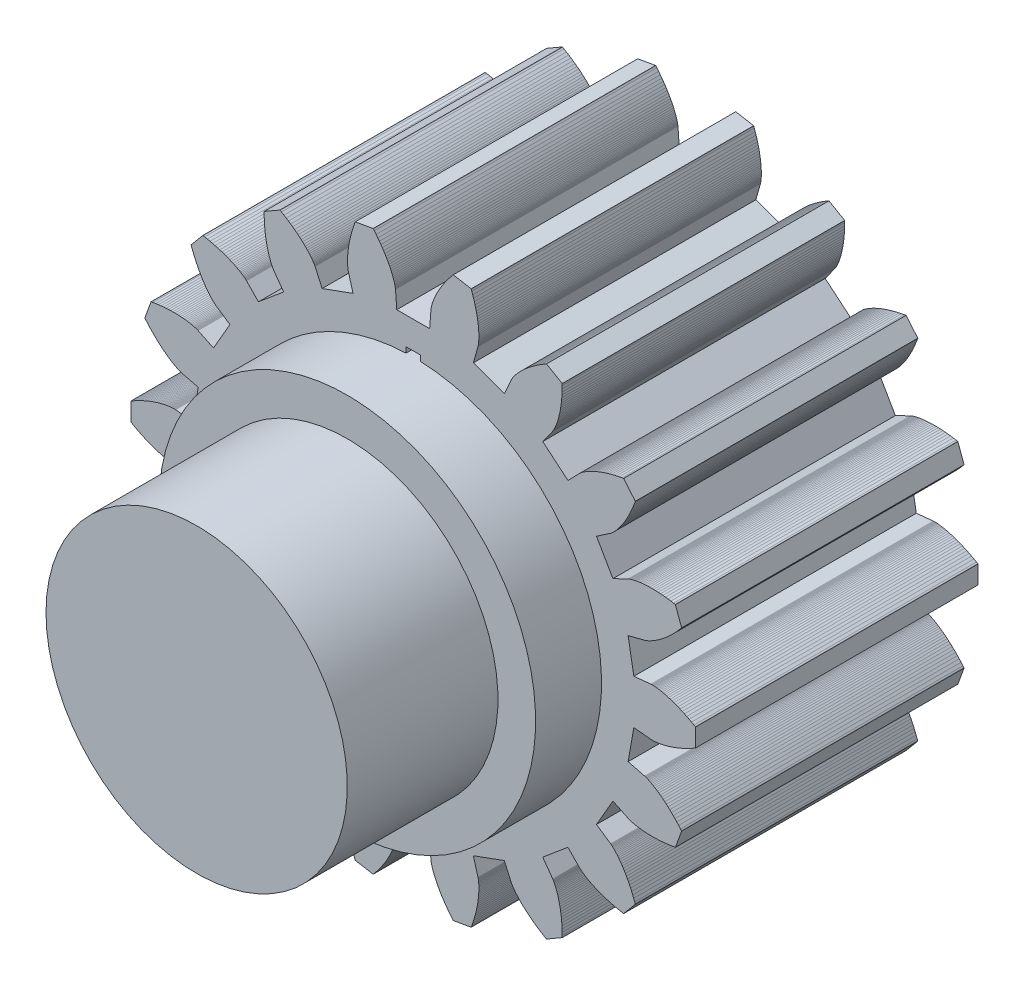
SolidWorks part; units mm, degrees
material "1.6587 (18CrNiMo7-6)"
ref_plane "Front Plane" through (0, 0, 0) normal (0, 0, 1) x (1, 0, 0)
ref_plane "Top Plane" through (0, 0, 0) normal (0, 1, 0) x (1, 0, 0)
ref_plane "Right Plane" through (0, 0, 0) normal (1, 0, 0) x (0, 0, -1)
sketch "SK_Sun_Root_Blank" plane through (0, 0, 0) normal (0, 0, 1) x (1, 0, 0)
  circle A0 centre (0, 0) radius 11.625
  dimension "D1" = 23.25
extrude "EX_Sun_Root_Blank" [suppressed] add sketch "SK_Sun_Root_Blank" along normal mid plane 15
sketch "SK_Sun_Gear_Profile_DXF" plane through (0, 0, 0) normal (0, 0, 1) x (1, 0, 0)
  line L0 (11.7158, -1.1788) -> (12.624, -1.2702)
  line L1 (12.624, -1.2702) -> (12.6307, -1.2707)
  line L2 (12.6307, -1.2707) -> (12.6421, -1.2713)
  line L3 (12.6421, -1.2713) -> (12.6583, -1.2718)
  line L4 (12.6583, -1.2718) -> (12.6793, -1.2721)
  line L5 (12.6793, -1.2721) -> (12.7051, -1.272)
  line L6 (12.7051, -1.272) -> (12.7356, -1.2713)
  line L7 (12.7356, -1.2713) -> (12.7709, -1.2697)
  line L8 (12.7709, -1.2697) -> (12.8109, -1.2672)
  line L9 (12.8109, -1.2672) -> (12.8556, -1.2635)
  line L10 (12.8556, -1.2635) -> (12.9049, -1.2585)
  line L11 (12.9049, -1.2585) -> (12.9589, -1.2519)
  line L12 (12.9589, -1.2519) -> (13.0175, -1.2437)
  line L13 (13.0175, -1.2437) -> (13.0806, -1.2335)
  line L14 (13.0806, -1.2335) -> (13.1482, -1.2213)
  line L15 (13.1482, -1.2213) -> (13.2202, -1.2068)
  line L16 (13.2202, -1.2068) -> (13.2966, -1.1899)
  line L17 (13.2966, -1.1899) -> (13.3773, -1.1704)
  line L18 (13.3773, -1.1704) -> (13.4622, -1.1481)
  line L19 (13.4622, -1.1481) -> (13.5513, -1.1229)
  line L20 (13.5513, -1.1229) -> (13.6444, -1.0945)
  line L21 (13.6444, -1.0945) -> (13.7415, -1.0629)
  line L22 (13.7415, -1.0629) -> (13.8424, -1.0279)
  line L23 (13.8424, -1.0279) -> (13.9471, -0.9892)
  line L24 (13.9471, -0.9892) -> (14.0555, -0.9468)
  line L25 (14.0555, -0.9468) -> (14.1675, -0.9005)
  line L26 (14.1675, -0.9005) -> (14.2829, -0.8501)
  line L27 (14.2829, -0.8501) -> (14.4017, -0.7954)
  line L28 (14.4017, -0.7954) -> (14.5237, -0.7364)
  line L29 (14.5237, -0.7364) -> (14.6487, -0.6729)
  line L30 (14.6487, -0.6729) -> (14.7767, -0.6048)
  line L31 (14.7767, -0.6048) -> (14.9076, -0.5318)
  line L32 (14.9076, -0.5318) -> (14.974, -0.4935)
  line L33 (14.974, -0.4935) -> (14.9907, -0.4837)
  line L34 (14.9907, -0.4837) -> (14.9917, -0.4831)
  line L35 (14.9917, -0.4831) -> (14.992, -0.4829)
  line L36 (14.992, -0.4829) -> (14.9922, -0.4828)
  line L37 (14.9922, -0.4828) -> (14.9922, 0.4828)
  line L38 (14.9922, 0.4828) -> (14.992, 0.4829)
  line L39 (14.992, 0.4829) -> (14.9917, 0.4831)
  line L40 (14.9917, 0.4831) -> (14.9907, 0.4837)
  line L41 (14.9907, 0.4837) -> (14.974, 0.4935)
  line L42 (14.974, 0.4935) -> (14.9076, 0.5318)
  line L43 (14.9076, 0.5318) -> (14.7767, 0.6048)
  line L44 (14.7767, 0.6048) -> (14.6487, 0.6729)
  line L45 (14.6487, 0.6729) -> (14.5237, 0.7364)
  line L46 (14.5237, 0.7364) -> (14.4017, 0.7954)
  line L47 (14.4017, 0.7954) -> (14.2829, 0.8501)
  line L48 (14.2829, 0.8501) -> (14.1675, 0.9005)
  line L49 (14.1675, 0.9005) -> (14.0555, 0.9468)
  line L50 (14.0555, 0.9468) -> (13.9471, 0.9892)
  line L51 (13.9471, 0.9892) -> (13.8424, 1.0279)
  line L52 (13.8424, 1.0279) -> (13.7415, 1.0629)
  line L53 (13.7415, 1.0629) -> (13.6444, 1.0945)
  line L54 (13.6444, 1.0945) -> (13.5513, 1.1229)
  line L55 (13.5513, 1.1229) -> (13.4622, 1.1481)
  line L56 (13.4622, 1.1481) -> (13.3773, 1.1704)
  line L57 (13.3773, 1.1704) -> (13.2966, 1.1899)
  line L58 (13.2966, 1.1899) -> (13.2202, 1.2068)
  line L59 (13.2202, 1.2068) -> (13.1482, 1.2213)
  line L60 (13.1482, 1.2213) -> (13.0806, 1.2335)
  line L61 (13.0806, 1.2335) -> (13.0175, 1.2437)
  line L62 (13.0175, 1.2437) -> (12.9589, 1.2519)
  line L63 (12.9589, 1.2519) -> (12.9049, 1.2585)
  line L64 (12.9049, 1.2585) -> (12.8556, 1.2635)
  line L65 (12.8556, 1.2635) -> (12.8109, 1.2672)
  line L66 (12.8109, 1.2672) -> (12.7709, 1.2697)
  line L67 (12.7709, 1.2697) -> (12.7356, 1.2713)
  line L68 (12.7356, 1.2713) -> (12.7051, 1.272)
  line L69 (12.7051, 1.272) -> (12.6793, 1.2721)
  line L70 (12.6793, 1.2721) -> (12.6583, 1.2718)
  line L71 (12.6583, 1.2718) -> (12.6421, 1.2713)
  line L72 (12.6421, 1.2713) -> (12.6307, 1.2707)
  line L73 (12.6307, 1.2707) -> (12.624, 1.2702)
  line L74 (12.624, 1.2702) -> (11.7158, 1.1788)
  line L75 (11.7158, 1.1788) -> (11.4125, 2.8993)
  line L76 (11.4125, 2.8993) -> (12.2971, 3.1241)
  line L77 (12.2971, 3.1241) -> (12.3036, 3.1259)
  line L78 (12.3036, 3.1259) -> (12.3145, 3.1293)
  line L79 (12.3145, 3.1293) -> (12.3299, 3.1343)
  line L80 (12.3299, 3.1343) -> (12.3498, 3.1412)
  line L81 (12.3498, 3.1412) -> (12.3739, 3.1501)
  line L82 (12.3739, 3.1501) -> (12.4024, 3.1612)
  line L83 (12.4024, 3.1612) -> (12.435, 3.1747)
  line L84 (12.435, 3.1747) -> (12.4717, 3.1908)
  line L85 (12.4717, 3.1908) -> (12.5125, 3.2095)
  line L86 (12.5125, 3.2095) -> (12.5571, 3.2311)
  line L87 (12.5571, 3.2311) -> (12.6056, 3.2558)
  line L88 (12.6056, 3.2558) -> (12.6578, 3.2836)
  line L89 (12.6578, 3.2836) -> (12.7136, 3.3147)
  line L90 (12.7136, 3.3147) -> (12.773, 3.3493)
  line L91 (12.773, 3.3493) -> (12.8357, 3.3876)
  line L92 (12.8357, 3.3876) -> (12.9017, 3.4296)
  line L93 (12.9017, 3.4296) -> (12.9709, 3.4755)
  line L94 (12.9709, 3.4755) -> (13.043, 3.5255)
  line L95 (13.043, 3.5255) -> (13.1181, 3.5797)
  line L96 (13.1181, 3.5797) -> (13.1959, 3.6381)
  line L97 (13.1959, 3.6381) -> (13.2763, 3.701)
  line L98 (13.2763, 3.701) -> (13.3592, 3.7685)
  line L99 (13.3592, 3.7685) -> (13.4444, 3.8406)
  line L100 (13.4444, 3.8406) -> (13.5317, 3.9176)
  line L101 (13.5317, 3.9176) -> (13.6211, 3.9994)
  line L102 (13.6211, 3.9994) -> (13.7123, 4.0863)
  line L103 (13.7123, 4.0863) -> (13.8052, 4.1782)
  line L104 (13.8052, 4.1782) -> (13.8996, 4.2754)
  line L105 (13.8996, 4.2754) -> (13.9954, 4.3778)
  line L106 (13.9954, 4.3778) -> (14.0924, 4.4856)
  line L107 (14.0924, 4.4856) -> (14.1904, 4.599)
  line L108 (14.1904, 4.599) -> (14.2397, 4.6577)
  line L109 (14.2397, 4.6577) -> (14.2521, 4.6726)
  line L110 (14.2521, 4.6726) -> (14.2529, 4.6735)
  line L111 (14.2529, 4.6735) -> (14.253, 4.6738)
  line L112 (14.253, 4.6738) -> (14.2532, 4.674)
  line L113 (14.2532, 4.674) -> (13.923, 5.5813)
  line L114 (13.923, 5.5813) -> (13.9227, 5.5814)
  line L115 (13.9227, 5.5814) -> (13.9224, 5.5814)
  line L116 (13.9224, 5.5814) -> (13.9212, 5.5817)
  line L117 (13.9212, 5.5817) -> (13.9022, 5.5851)
  line L118 (13.9022, 5.5851) -> (13.8266, 5.5984)
  line L119 (13.8266, 5.5984) -> (13.6787, 5.6222)
  line L120 (13.6787, 5.6222) -> (13.5351, 5.6425)
  line L121 (13.5351, 5.6425) -> (13.3959, 5.6594)
  line L122 (13.3959, 5.6594) -> (13.2611, 5.6731)
  line L123 (13.2611, 5.6731) -> (13.1308, 5.6838)
  line L124 (13.1308, 5.6838) -> (13.0051, 5.6917)
  line L125 (13.0051, 5.6917) -> (12.8841, 5.697)
  line L126 (12.8841, 5.697) -> (12.7677, 5.6998)
  line L127 (12.7677, 5.6998) -> (12.6561, 5.7003)
  line L128 (12.6561, 5.7003) -> (12.5492, 5.6987)
  line L129 (12.5492, 5.6987) -> (12.4472, 5.6952)
  line L130 (12.4472, 5.6952) -> (12.35, 5.69)
  line L131 (12.35, 5.69) -> (12.2577, 5.6832)
  line L132 (12.2577, 5.6832) -> (12.1703, 5.6751)
  line L133 (12.1703, 5.6751) -> (12.0878, 5.6658)
  line L134 (12.0878, 5.6658) -> (12.0102, 5.6556)
  line L135 (12.0102, 5.6556) -> (11.9376, 5.6446)
  line L136 (11.9376, 5.6446) -> (11.8699, 5.633)
  line L137 (11.8699, 5.633) -> (11.8071, 5.6209)
  line L138 (11.8071, 5.6209) -> (11.7492, 5.6087)
  line L139 (11.7492, 5.6087) -> (11.6962, 5.5964)
  line L140 (11.6962, 5.5964) -> (11.6481, 5.5842)
  line L141 (11.6481, 5.5842) -> (11.6049, 5.5724)
  line L142 (11.6049, 5.5724) -> (11.5664, 5.5611)
  line L143 (11.5664, 5.5611) -> (11.5328, 5.5504)
  line L144 (11.5328, 5.5504) -> (11.5038, 5.5407)
  line L145 (11.5038, 5.5407) -> (11.4796, 5.532)
  line L146 (11.4796, 5.532) -> (11.46, 5.5245)
  line L147 (11.46, 5.5245) -> (11.4449, 5.5185)
  line L148 (11.4449, 5.5185) -> (11.4344, 5.514)
  line L149 (11.4344, 5.514) -> (11.4283, 5.5113)
  line L150 (11.4283, 5.5113) -> (10.6061, 5.1148)
  line L151 (10.6061, 5.1148) -> (9.7326, 6.6278)
  line L152 (9.7326, 6.6278) -> (10.487, 7.1416)
  line L153 (10.487, 7.1416) -> (10.4924, 7.1455)
  line L154 (10.4924, 7.1455) -> (10.5016, 7.1524)
  line L155 (10.5016, 7.1524) -> (10.5144, 7.1624)
  line L156 (10.5144, 7.1624) -> (10.5306, 7.1756)
  line L157 (10.5306, 7.1756) -> (10.5503, 7.1923)
  line L158 (10.5503, 7.1923) -> (10.5732, 7.2125)
  line L159 (10.5732, 7.2125) -> (10.5992, 7.2363)
  line L160 (10.5992, 7.2363) -> (10.6283, 7.2639)
  line L161 (10.6283, 7.2639) -> (10.6601, 7.2955)
  line L162 (10.6601, 7.2955) -> (10.6947, 7.3311)
  line L163 (10.6947, 7.3311) -> (10.7319, 7.3708)
  line L164 (10.7319, 7.3708) -> (10.7714, 7.4148)
  line L165 (10.7714, 7.4148) -> (10.8132, 7.4631)
  line L166 (10.8132, 7.4631) -> (10.8571, 7.516)
  line L167 (10.8571, 7.516) -> (10.903, 7.5734)
  line L168 (10.903, 7.5734) -> (10.9506, 7.6354)
  line L169 (10.9506, 7.6354) -> (10.9999, 7.7022)
  line L170 (10.9999, 7.7022) -> (11.0506, 7.7739)
  line L171 (11.0506, 7.7739) -> (11.1026, 7.8504)
  line L172 (11.1026, 7.8504) -> (11.1558, 7.932)
  line L173 (11.1558, 7.932) -> (11.2098, 8.0186)
  line L174 (11.2098, 8.0186) -> (11.2646, 8.1103)
  line L175 (11.2646, 8.1103) -> (11.32, 8.2073)
  line L176 (11.32, 8.2073) -> (11.3758, 8.3094)
  line L177 (11.3758, 8.3094) -> (11.4317, 8.4169)
  line L178 (11.4317, 8.4169) -> (11.4878, 8.5297)
  line L179 (11.4878, 8.5297) -> (11.5436, 8.6479)
  line L180 (11.5436, 8.6479) -> (11.5991, 8.7715)
  line L181 (11.5991, 8.7715) -> (11.6541, 8.9005)
  line L182 (11.6541, 8.9005) -> (11.7084, 9.035)
  line L183 (11.7084, 9.035) -> (11.7617, 9.175)
  line L184 (11.7617, 9.175) -> (11.7879, 9.2471)
  line L185 (11.7879, 9.2471) -> (11.7945, 9.2653)
  line L186 (11.7945, 9.2653) -> (11.7949, 9.2664)
  line L187 (11.7949, 9.2664) -> (11.795, 9.2667)
  line L188 (11.795, 9.2667) -> (11.795, 9.267)
  line L189 (11.795, 9.267) -> (11.1744, 10.0067)
  line L190 (11.1744, 10.0067) -> (11.1741, 10.0066)
  line L191 (11.1741, 10.0066) -> (11.1738, 10.0066)
  line L192 (11.1738, 10.0066) -> (11.1726, 10.0064)
  line L193 (11.1726, 10.0064) -> (11.1535, 10.0031)
  line L194 (11.1535, 10.0031) -> (11.078, 9.9898)
  line L195 (11.078, 9.9898) -> (10.9309, 9.9616)
  line L196 (10.9309, 9.9616) -> (10.789, 9.9315)
  line L197 (10.789, 9.9315) -> (10.6524, 9.8998)
  line L198 (10.6524, 9.8998) -> (10.521, 9.8666)
  line L199 (10.521, 9.8666) -> (10.395, 9.8321)
  line L200 (10.395, 9.8321) -> (10.2741, 9.7965)
  line L201 (10.2741, 9.7965) -> (10.1586, 9.76)
  line L202 (10.1586, 9.76) -> (10.0483, 9.7228)
  line L203 (10.0483, 9.7228) -> (9.9432, 9.6851)
  line L204 (9.9432, 9.6851) -> (9.8433, 9.6471)
  line L205 (9.8433, 9.6471) -> (9.7487, 9.6089)
  line L206 (9.7487, 9.6089) -> (9.6591, 9.5708)
  line L207 (9.6591, 9.5708) -> (9.5747, 9.5328)
  line L208 (9.5747, 9.5328) -> (9.4953, 9.4953)
  line L209 (9.4953, 9.4953) -> (9.421, 9.4584)
  line L210 (9.421, 9.4584) -> (9.3516, 9.4223)
  line L211 (9.3516, 9.4223) -> (9.2871, 9.3871)
  line L212 (9.2871, 9.3871) -> (9.2275, 9.353)
  line L213 (9.2275, 9.353) -> (9.1726, 9.3202)
  line L214 (9.1726, 9.3202) -> (9.1224, 9.2889)
  line L215 (9.1224, 9.2889) -> (9.0768, 9.2592)
  line L216 (9.0768, 9.2592) -> (9.0358, 9.2313)
  line L217 (9.0358, 9.2313) -> (8.9992, 9.2054)
  line L218 (8.9992, 9.2054) -> (8.9669, 9.1816)
  line L219 (8.9669, 9.1816) -> (8.9389, 9.1601)
  line L220 (8.9389, 9.1601) -> (8.915, 9.1411)
  line L221 (8.915, 9.1411) -> (8.8952, 9.1246)
  line L222 (8.8952, 9.1246) -> (8.8793, 9.1109)
  line L223 (8.8793, 9.1109) -> (8.8673, 9.1001)
  line L224 (8.8673, 9.1001) -> (8.8589, 9.0922)
  line L225 (8.8589, 9.0922) -> (8.8541, 9.0876)
  line L226 (8.8541, 9.0876) -> (8.2171, 8.4338)
  line L227 (8.2171, 8.4338) -> (6.8788, 9.5568)
  line L228 (6.8788, 9.5568) -> (7.412, 10.2977)
  line L229 (7.412, 10.2977) -> (7.4158, 10.3032)
  line L230 (7.4158, 10.3032) -> (7.422, 10.3128)
  line L231 (7.422, 10.3128) -> (7.4306, 10.3265)
  line L232 (7.4306, 10.3265) -> (7.4414, 10.3446)
  line L233 (7.4414, 10.3446) -> (7.4541, 10.3669)
  line L234 (7.4541, 10.3669) -> (7.4688, 10.3937)
  line L235 (7.4688, 10.3937) -> (7.4851, 10.4251)
  line L236 (7.4851, 10.4251) -> (7.5029, 10.4609)
  line L237 (7.5029, 10.4609) -> (7.522, 10.5015)
  line L238 (7.522, 10.5015) -> (7.5424, 10.5468)
  line L239 (7.5424, 10.5468) -> (7.5637, 10.5968)
  line L240 (7.5637, 10.5968) -> (7.5858, 10.6517)
  line L241 (7.5858, 10.6517) -> (7.6086, 10.7114)
  line L242 (7.6086, 10.7114) -> (7.6318, 10.7761)
  line L243 (7.6318, 10.7761) -> (7.6552, 10.8457)
  line L244 (7.6552, 10.8457) -> (7.6788, 10.9203)
  line L245 (7.6788, 10.9203) -> (7.7022, 10.9999)
  line L246 (7.7022, 10.9999) -> (7.7254, 11.0846)
  line L247 (7.7254, 11.0846) -> (7.7481, 11.1743)
  line L248 (7.7481, 11.1743) -> (7.7701, 11.2691)
  line L249 (7.7701, 11.2691) -> (7.7912, 11.369)
  line L250 (7.7912, 11.369) -> (7.8114, 11.4739)
  line L251 (7.8114, 11.4739) -> (7.8303, 11.584)
  line L252 (7.8303, 11.584) -> (7.8477, 11.6991)
  line L253 (7.8477, 11.6991) -> (7.8636, 11.8192)
  line L254 (7.8636, 11.8192) -> (7.8776, 11.9444)
  line L255 (7.8776, 11.9444) -> (7.8897, 12.0745)
  line L256 (7.8897, 12.0745) -> (7.8996, 12.2096)
  line L257 (7.8996, 12.2096) -> (7.9071, 12.3497)
  line L258 (7.9071, 12.3497) -> (7.9121, 12.4946)
  line L259 (7.9121, 12.4946) -> (7.9143, 12.6444)
  line L260 (7.9143, 12.6444) -> (7.9144, 12.7211)
  line L261 (7.9144, 12.7211) -> (7.9142, 12.7405)
  line L262 (7.9142, 12.7405) -> (7.9142, 12.7417)
  line L263 (7.9142, 12.7417) -> (7.9142, 12.742)
  line L264 (7.9142, 12.742) -> (7.9142, 12.7423)
  line L265 (7.9142, 12.7423) -> (7.078, 13.225)
  line L266 (7.078, 13.225) -> (7.0778, 13.2249)
  line L267 (7.0778, 13.2249) -> (7.0775, 13.2248)
  line L268 (7.0775, 13.2248) -> (7.0764, 13.2242)
  line L269 (7.0764, 13.2242) -> (7.0596, 13.2146)
  line L270 (7.0596, 13.2146) -> (6.9932, 13.1762)
  line L271 (6.9932, 13.1762) -> (6.8646, 13.0994)
  line L272 (6.8646, 13.0994) -> (6.7416, 13.0226)
  line L273 (6.7416, 13.0226) -> (6.6241, 12.9461)
  line L274 (6.6241, 12.9461) -> (6.512, 12.8699)
  line L275 (6.512, 12.8699) -> (6.4053, 12.7944)
  line L276 (6.4053, 12.7944) -> (6.3039, 12.7197)
  line L277 (6.3039, 12.7197) -> (6.2078, 12.6459)
  line L278 (6.2078, 12.6459) -> (6.1169, 12.5732)
  line L279 (6.1169, 12.5732) -> (6.031, 12.5018)
  line L280 (6.031, 12.5018) -> (5.9502, 12.4319)
  line L281 (5.9502, 12.4319) -> (5.8743, 12.3636)
  line L282 (5.8743, 12.3636) -> (5.8032, 12.2972)
  line L283 (5.8032, 12.2972) -> (5.7368, 12.2327)
  line L284 (5.7368, 12.2327) -> (5.6751, 12.1703)
  line L285 (5.6751, 12.1703) -> (5.6179, 12.1102)
  line L286 (5.6179, 12.1102) -> (5.565, 12.0525)
  line L287 (5.565, 12.0525) -> (5.5165, 11.9973)
  line L288 (5.5165, 11.9973) -> (5.4721, 11.9449)
  line L289 (5.4721, 11.9449) -> (5.4317, 11.8953)
  line L290 (5.4317, 11.8953) -> (5.3952, 11.8487)
  line L291 (5.3952, 11.8487) -> (5.3626, 11.8053)
  line L292 (5.3626, 11.8053) -> (5.3335, 11.765)
  line L293 (5.3335, 11.765) -> (5.308, 11.7282)
  line L294 (5.308, 11.7282) -> (5.2858, 11.6948)
  line L295 (5.2858, 11.6948) -> (5.2669, 11.665)
  line L296 (5.2669, 11.665) -> (5.251, 11.6389)
  line L297 (5.251, 11.6389) -> (5.238, 11.6167)
  line L298 (5.238, 11.6167) -> (5.2277, 11.5984)
  line L299 (5.2277, 11.5984) -> (5.2201, 11.584)
  line L300 (5.2201, 11.584) -> (5.2149, 11.5738)
  line L301 (5.2149, 11.5738) -> (5.212, 11.5678)
  line L302 (5.212, 11.5678) -> (4.837, 10.7356)
  line L303 (4.837, 10.7356) -> (3.1953, 11.3332)
  line L304 (3.1953, 11.3332) -> (3.443, 12.2117)
  line L305 (3.443, 12.2117) -> (3.4447, 12.2182)
  line L306 (3.4447, 12.2182) -> (3.4472, 12.2293)
  line L307 (3.4472, 12.2293) -> (3.4506, 12.2452)
  line L308 (3.4506, 12.2452) -> (3.4545, 12.2658)
  line L309 (3.4545, 12.2658) -> (3.4589, 12.2912)
  line L310 (3.4589, 12.2912) -> (3.4635, 12.3214)
  line L311 (3.4635, 12.3214) -> (3.4681, 12.3564)
  line L312 (3.4681, 12.3564) -> (3.4726, 12.3962)
  line L313 (3.4726, 12.3962) -> (3.4767, 12.4409)
  line L314 (3.4767, 12.4409) -> (3.4803, 12.4903)
  line L315 (3.4803, 12.4903) -> (3.4832, 12.5447)
  line L316 (3.4832, 12.5447) -> (3.4852, 12.6038)
  line L317 (3.4852, 12.6038) -> (3.4862, 12.6677)
  line L318 (3.4862, 12.6677) -> (3.4859, 12.7364)
  line L319 (3.4859, 12.7364) -> (3.4841, 12.8098)
  line L320 (3.4841, 12.8098) -> (3.4807, 12.888)
  line L321 (3.4807, 12.888) -> (3.4755, 12.9709)
  line L322 (3.4755, 12.9709) -> (3.4683, 13.0583)
  line L323 (3.4683, 13.0583) -> (3.459, 13.1504)
  line L324 (3.459, 13.1504) -> (3.4472, 13.247)
  line L325 (3.4472, 13.247) -> (3.4329, 13.3481)
  line L326 (3.4329, 13.3481) -> (3.416, 13.4536)
  line L327 (3.416, 13.4536) -> (3.3961, 13.5635)
  line L328 (3.3961, 13.5635) -> (3.3731, 13.6776)
  line L329 (3.3731, 13.6776) -> (3.3469, 13.7959)
  line L330 (3.3469, 13.7959) -> (3.3173, 13.9183)
  line L331 (3.3173, 13.9183) -> (3.2842, 14.0448)
  line L332 (3.2842, 14.0448) -> (3.2473, 14.1751)
  line L333 (3.2473, 14.1751) -> (3.2064, 14.3093)
  line L334 (3.2064, 14.3093) -> (3.1615, 14.4472)
  line L335 (3.1615, 14.4472) -> (3.1124, 14.5887)
  line L336 (3.1124, 14.5887) -> (3.0862, 14.6608)
  line L337 (3.0862, 14.6608) -> (3.0795, 14.679)
  line L338 (3.0795, 14.679) -> (3.079, 14.6801)
  line L339 (3.079, 14.6801) -> (3.0789, 14.6804)
  line L340 (3.0789, 14.6804) -> (3.0788, 14.6806)
  line L341 (3.0788, 14.6806) -> (2.1279, 14.8483)
  line L342 (2.1279, 14.8483) -> (2.1277, 14.8481)
  line L343 (2.1277, 14.8481) -> (2.1275, 14.8479)
  line L344 (2.1275, 14.8479) -> (2.1267, 14.8469)
  line L345 (2.1267, 14.8469) -> (2.1142, 14.8322)
  line L346 (2.1142, 14.8322) -> (2.0649, 14.7734)
  line L347 (2.0649, 14.7734) -> (1.9704, 14.6572)
  line L348 (1.9704, 14.6572) -> (1.881, 14.543)
  line L349 (1.881, 14.543) -> (1.7968, 14.4309)
  line L350 (1.7968, 14.4309) -> (1.7175, 14.321)
  line L351 (1.7175, 14.321) -> (1.6431, 14.2136)
  line L352 (1.6431, 14.2136) -> (1.5734, 14.1086)
  line L353 (1.5734, 14.1086) -> (1.5083, 14.0064)
  line L354 (1.5083, 14.0064) -> (1.4477, 13.907)
  line L355 (1.4477, 13.907) -> (1.3915, 13.8106)
  line L356 (1.3915, 13.8106) -> (1.3394, 13.7173)
  line L357 (1.3394, 13.7173) -> (1.2914, 13.6272)
  line L358 (1.2914, 13.6272) -> (1.2474, 13.5404)
  line L359 (1.2474, 13.5404) -> (1.207, 13.4571)
  line L360 (1.207, 13.4571) -> (1.1704, 13.3773)
  line L361 (1.1704, 13.3773) -> (1.1371, 13.3012)
  line L362 (1.1371, 13.3012) -> (1.1072, 13.229)
  line L363 (1.1072, 13.229) -> (1.0804, 13.1605)
  line L364 (1.0804, 13.1605) -> (1.0567, 13.0961)
  line L365 (1.0567, 13.0961) -> (1.0357, 13.0357)
  line L366 (1.0357, 13.0357) -> (1.0174, 12.9795)
  line L367 (1.0174, 12.9795) -> (1.0015, 12.9274)
  line L368 (1.0015, 12.9274) -> (0.988, 12.8797)
  line L369 (0.988, 12.8797) -> (0.9766, 12.8363)
  line L370 (0.9766, 12.8363) -> (0.9672, 12.7974)
  line L371 (0.9672, 12.7974) -> (0.9596, 12.7629)
  line L372 (0.9596, 12.7629) -> (0.9535, 12.733)
  line L373 (0.9535, 12.733) -> (0.9489, 12.7076)
  line L374 (0.9489, 12.7076) -> (0.9456, 12.6869)
  line L375 (0.9456, 12.6869) -> (0.9433, 12.6708)
  line L376 (0.9433, 12.6708) -> (0.9419, 12.6595)
  line L377 (0.9419, 12.6595) -> (0.9413, 12.6528)
  line L378 (0.9413, 12.6528) -> (0.8735, 11.7426)
  line L379 (0.8735, 11.7426) -> (-0.8735, 11.7426)
  line L380 (-0.8735, 11.7426) -> (-0.9413, 12.6528)
  line L381 (-0.9413, 12.6528) -> (-0.9419, 12.6595)
  line L382 (-0.9419, 12.6595) -> (-0.9433, 12.6708)
  line L383 (-0.9433, 12.6708) -> (-0.9456, 12.6869)
  line L384 (-0.9456, 12.6869) -> (-0.9489, 12.7076)
  line L385 (-0.9489, 12.7076) -> (-0.9535, 12.733)
  line L386 (-0.9535, 12.733) -> (-0.9596, 12.7629)
  line L387 (-0.9596, 12.7629) -> (-0.9672, 12.7974)
  line L388 (-0.9672, 12.7974) -> (-0.9766, 12.8363)
  line L389 (-0.9766, 12.8363) -> (-0.988, 12.8797)
  line L390 (-0.988, 12.8797) -> (-1.0015, 12.9274)
  line L391 (-1.0015, 12.9274) -> (-1.0174, 12.9795)
  line L392 (-1.0174, 12.9795) -> (-1.0357, 13.0357)
  line L393 (-1.0357, 13.0357) -> (-1.0567, 13.0961)
  line L394 (-1.0567, 13.0961) -> (-1.0804, 13.1605)
  line L395 (-1.0804, 13.1605) -> (-1.1072, 13.229)
  line L396 (-1.1072, 13.229) -> (-1.1371, 13.3012)
  line L397 (-1.1371, 13.3012) -> (-1.1704, 13.3773)
  line L398 (-1.1704, 13.3773) -> (-1.2071, 13.4571)
  line L399 (-1.2071, 13.4571) -> (-1.2474, 13.5404)
  line L400 (-1.2474, 13.5404) -> (-1.2914, 13.6272)
  line L401 (-1.2914, 13.6272) -> (-1.3394, 13.7173)
  line L402 (-1.3394, 13.7173) -> (-1.3915, 13.8106)
  line L403 (-1.3915, 13.8106) -> (-1.4477, 13.907)
  line L404 (-1.4477, 13.907) -> (-1.5083, 14.0064)
  line L405 (-1.5083, 14.0064) -> (-1.5734, 14.1086)
  line L406 (-1.5734, 14.1086) -> (-1.6431, 14.2136)
  line L407 (-1.6431, 14.2136) -> (-1.7175, 14.321)
  line L408 (-1.7175, 14.321) -> (-1.7968, 14.4309)
  line L409 (-1.7968, 14.4309) -> (-1.881, 14.543)
  line L410 (-1.881, 14.543) -> (-1.9704, 14.6572)
  line L411 (-1.9704, 14.6572) -> (-2.0649, 14.7734)
  line L412 (-2.0649, 14.7734) -> (-2.1142, 14.8322)
  line L413 (-2.1142, 14.8322) -> (-2.1267, 14.8469)
  line L414 (-2.1267, 14.8469) -> (-2.1275, 14.8479)
  line L415 (-2.1275, 14.8479) -> (-2.1277, 14.8481)
  line L416 (-2.1277, 14.8481) -> (-2.1279, 14.8483)
  line L417 (-2.1279, 14.8483) -> (-3.0788, 14.6806)
  line L418 (-3.0788, 14.6806) -> (-3.0789, 14.6804)
  line L419 (-3.0789, 14.6804) -> (-3.079, 14.6801)
  line L420 (-3.079, 14.6801) -> (-3.0795, 14.679)
  line L421 (-3.0795, 14.679) -> (-3.0862, 14.6608)
  line L422 (-3.0862, 14.6608) -> (-3.1124, 14.5887)
  line L423 (-3.1124, 14.5887) -> (-3.1615, 14.4472)
  line L424 (-3.1615, 14.4472) -> (-3.2064, 14.3093)
  line L425 (-3.2064, 14.3093) -> (-3.2473, 14.1751)
  line L426 (-3.2473, 14.1751) -> (-3.2842, 14.0448)
  line L427 (-3.2842, 14.0448) -> (-3.3173, 13.9183)
  line L428 (-3.3173, 13.9183) -> (-3.3469, 13.7959)
  line L429 (-3.3469, 13.7959) -> (-3.3731, 13.6776)
  line L430 (-3.3731, 13.6776) -> (-3.3961, 13.5635)
  line L431 (-3.3961, 13.5635) -> (-3.416, 13.4536)
  line L432 (-3.416, 13.4536) -> (-3.4329, 13.3481)
  line L433 (-3.4329, 13.3481) -> (-3.4472, 13.247)
  line L434 (-3.4472, 13.247) -> (-3.459, 13.1504)
  line L435 (-3.459, 13.1504) -> (-3.4683, 13.0583)
  line L436 (-3.4683, 13.0583) -> (-3.4755, 12.9709)
  line L437 (-3.4755, 12.9709) -> (-3.4807, 12.888)
  line L438 (-3.4807, 12.888) -> (-3.4841, 12.8098)
  line L439 (-3.4841, 12.8098) -> (-3.4859, 12.7364)
  line L440 (-3.4859, 12.7364) -> (-3.4862, 12.6677)
  line L441 (-3.4862, 12.6677) -> (-3.4852, 12.6038)
  line L442 (-3.4852, 12.6038) -> (-3.4832, 12.5447)
  line L443 (-3.4832, 12.5447) -> (-3.4803, 12.4903)
  line L444 (-3.4803, 12.4903) -> (-3.4767, 12.4409)
  line L445 (-3.4767, 12.4409) -> (-3.4726, 12.3962)
  line L446 (-3.4726, 12.3962) -> (-3.4681, 12.3564)
  line L447 (-3.4681, 12.3564) -> (-3.4635, 12.3214)
  line L448 (-3.4635, 12.3214) -> (-3.4589, 12.2912)
  line L449 (-3.4589, 12.2912) -> (-3.4545, 12.2658)
  line L450 (-3.4545, 12.2658) -> (-3.4506, 12.2452)
  line L451 (-3.4506, 12.2452) -> (-3.4472, 12.2293)
  line L452 (-3.4472, 12.2293) -> (-3.4447, 12.2182)
  line L453 (-3.4447, 12.2182) -> (-3.443, 12.2117)
  line L454 (-3.443, 12.2117) -> (-3.1953, 11.3332)
  line L455 (-3.1953, 11.3332) -> (-4.837, 10.7356)
  line L456 (-4.837, 10.7356) -> (-5.212, 11.5678)
  line L457 (-5.212, 11.5678) -> (-5.2149, 11.5738)
  line L458 (-5.2149, 11.5738) -> (-5.2201, 11.584)
  line L459 (-5.2201, 11.584) -> (-5.2277, 11.5984)
  line L460 (-5.2277, 11.5984) -> (-5.238, 11.6167)
  line L461 (-5.238, 11.6167) -> (-5.251, 11.6389)
  line L462 (-5.251, 11.6389) -> (-5.2669, 11.665)
  line L463 (-5.2669, 11.665) -> (-5.2858, 11.6948)
  line L464 (-5.2858, 11.6948) -> (-5.308, 11.7282)
  line L465 (-5.308, 11.7282) -> (-5.3335, 11.765)
  line L466 (-5.3335, 11.765) -> (-5.3626, 11.8053)
  line L467 (-5.3626, 11.8053) -> (-5.3952, 11.8487)
  line L468 (-5.3952, 11.8487) -> (-5.4317, 11.8953)
  line L469 (-5.4317, 11.8953) -> (-5.4721, 11.9449)
  line L470 (-5.4721, 11.9449) -> (-5.5165, 11.9973)
  line L471 (-5.5165, 11.9973) -> (-5.565, 12.0525)
  line L472 (-5.565, 12.0525) -> (-5.6179, 12.1102)
  line L473 (-5.6179, 12.1102) -> (-5.6751, 12.1703)
  line L474 (-5.6751, 12.1703) -> (-5.7368, 12.2327)
  line L475 (-5.7368, 12.2327) -> (-5.8032, 12.2972)
  line L476 (-5.8032, 12.2972) -> (-5.8743, 12.3636)
  line L477 (-5.8743, 12.3636) -> (-5.9502, 12.4319)
  line L478 (-5.9502, 12.4319) -> (-6.031, 12.5018)
  line L479 (-6.031, 12.5018) -> (-6.1169, 12.5732)
  line L480 (-6.1169, 12.5732) -> (-6.2078, 12.6459)
  line L481 (-6.2078, 12.6459) -> (-6.3039, 12.7197)
  line L482 (-6.3039, 12.7197) -> (-6.4053, 12.7944)
  line L483 (-6.4053, 12.7944) -> (-6.512, 12.8699)
  line L484 (-6.512, 12.8699) -> (-6.6241, 12.9461)
  line L485 (-6.6241, 12.9461) -> (-6.7416, 13.0226)
  line L486 (-6.7416, 13.0226) -> (-6.8646, 13.0994)
  line L487 (-6.8646, 13.0994) -> (-6.9932, 13.1762)
  line L488 (-6.9932, 13.1762) -> (-7.0596, 13.2146)
  line L489 (-7.0596, 13.2146) -> (-7.0764, 13.2242)
  line L490 (-7.0764, 13.2242) -> (-7.0775, 13.2248)
  line L491 (-7.0775, 13.2248) -> (-7.0778, 13.2249)
  line L492 (-7.0778, 13.2249) -> (-7.078, 13.225)
  line L493 (-7.078, 13.225) -> (-7.9142, 12.7423)
  line L494 (-7.9142, 12.7423) -> (-7.9142, 12.742)
  line L495 (-7.9142, 12.742) -> (-7.9142, 12.7417)
  line L496 (-7.9142, 12.7417) -> (-7.9142, 12.7405)
  line L497 (-7.9142, 12.7405) -> (-7.9144, 12.7211)
  line L498 (-7.9144, 12.7211) -> (-7.9143, 12.6444)
  line L499 (-7.9143, 12.6444) -> (-7.9121, 12.4946)
  line L500 (-7.9121, 12.4946) -> (-7.9071, 12.3497)
  line L501 (-7.9071, 12.3497) -> (-7.8996, 12.2096)
  line L502 (-7.8996, 12.2096) -> (-7.8897, 12.0745)
  line L503 (-7.8897, 12.0745) -> (-7.8776, 11.9444)
  line L504 (-7.8776, 11.9444) -> (-7.8636, 11.8192)
  line L505 (-7.8636, 11.8192) -> (-7.8477, 11.6991)
  line L506 (-7.8477, 11.6991) -> (-7.8303, 11.584)
  line L507 (-7.8303, 11.584) -> (-7.8114, 11.4739)
  line L508 (-7.8114, 11.4739) -> (-7.7912, 11.369)
  line L509 (-7.7912, 11.369) -> (-7.7701, 11.2691)
  line L510 (-7.7701, 11.2691) -> (-7.7481, 11.1743)
  line L511 (-7.7481, 11.1743) -> (-7.7254, 11.0846)
  line L512 (-7.7254, 11.0846) -> (-7.7022, 10.9999)
  line L513 (-7.7022, 10.9999) -> (-7.6788, 10.9203)
  line L514 (-7.6788, 10.9203) -> (-7.6552, 10.8457)
  line L515 (-7.6552, 10.8457) -> (-7.6318, 10.7761)
  line L516 (-7.6318, 10.7761) -> (-7.6086, 10.7114)
  line L517 (-7.6086, 10.7114) -> (-7.5858, 10.6517)
  line L518 (-7.5858, 10.6517) -> (-7.5637, 10.5968)
  line L519 (-7.5637, 10.5968) -> (-7.5424, 10.5468)
  line L520 (-7.5424, 10.5468) -> (-7.522, 10.5015)
  line L521 (-7.522, 10.5015) -> (-7.5029, 10.4609)
  line L522 (-7.5029, 10.4609) -> (-7.4851, 10.4251)
  line L523 (-7.4851, 10.4251) -> (-7.4688, 10.3937)
  line L524 (-7.4688, 10.3937) -> (-7.4541, 10.3669)
  line L525 (-7.4541, 10.3669) -> (-7.4414, 10.3446)
  line L526 (-7.4414, 10.3446) -> (-7.4306, 10.3265)
  line L527 (-7.4306, 10.3265) -> (-7.422, 10.3128)
  line L528 (-7.422, 10.3128) -> (-7.4158, 10.3032)
  line L529 (-7.4158, 10.3032) -> (-7.412, 10.2977)
  line L530 (-7.412, 10.2977) -> (-6.8788, 9.5568)
  line L531 (-6.8788, 9.5568) -> (-8.2171, 8.4338)
  line L532 (-8.2171, 8.4338) -> (-8.8541, 9.0876)
  line L533 (-8.8541, 9.0876) -> (-8.8589, 9.0922)
  line L534 (-8.8589, 9.0922) -> (-8.8673, 9.1001)
  line L535 (-8.8673, 9.1001) -> (-8.8793, 9.1109)
  line L536 (-8.8793, 9.1109) -> (-8.8952, 9.1246)
  line L537 (-8.8952, 9.1246) -> (-8.915, 9.1411)
  line L538 (-8.915, 9.1411) -> (-8.9389, 9.1601)
  line L539 (-8.9389, 9.1601) -> (-8.9669, 9.1816)
  line L540 (-8.9669, 9.1816) -> (-8.9992, 9.2054)
  line L541 (-8.9992, 9.2054) -> (-9.0358, 9.2313)
  line L542 (-9.0358, 9.2313) -> (-9.0768, 9.2592)
  line L543 (-9.0768, 9.2592) -> (-9.1224, 9.2889)
  line L544 (-9.1224, 9.2889) -> (-9.1726, 9.3202)
  line L545 (-9.1726, 9.3202) -> (-9.2275, 9.353)
  line L546 (-9.2275, 9.353) -> (-9.2871, 9.3871)
  line L547 (-9.2871, 9.3871) -> (-9.3516, 9.4223)
  line L548 (-9.3516, 9.4223) -> (-9.421, 9.4584)
  line L549 (-9.421, 9.4584) -> (-9.4953, 9.4953)
  line L550 (-9.4953, 9.4953) -> (-9.5747, 9.5328)
  line L551 (-9.5747, 9.5328) -> (-9.6591, 9.5708)
  line L552 (-9.6591, 9.5708) -> (-9.7487, 9.6089)
  line L553 (-9.7487, 9.6089) -> (-9.8433, 9.6471)
  line L554 (-9.8433, 9.6471) -> (-9.9432, 9.6851)
  line L555 (-9.9432, 9.6851) -> (-10.0483, 9.7228)
  line L556 (-10.0483, 9.7228) -> (-10.1586, 9.76)
  line L557 (-10.1586, 9.76) -> (-10.2741, 9.7965)
  line L558 (-10.2741, 9.7965) -> (-10.395, 9.8321)
  line L559 (-10.395, 9.8321) -> (-10.521, 9.8666)
  line L560 (-10.521, 9.8666) -> (-10.6524, 9.8998)
  line L561 (-10.6524, 9.8998) -> (-10.789, 9.9315)
  line L562 (-10.789, 9.9315) -> (-10.9309, 9.9616)
  line L563 (-10.9309, 9.9616) -> (-11.078, 9.9898)
  line L564 (-11.078, 9.9898) -> (-11.1535, 10.0031)
  line L565 (-11.1535, 10.0031) -> (-11.1726, 10.0064)
  line L566 (-11.1726, 10.0064) -> (-11.1738, 10.0066)
  line L567 (-11.1738, 10.0066) -> (-11.1741, 10.0066)
  line L568 (-11.1741, 10.0066) -> (-11.1744, 10.0067)
  line L569 (-11.1744, 10.0067) -> (-11.795, 9.267)
  line L570 (-11.795, 9.267) -> (-11.795, 9.2667)
  line L571 (-11.795, 9.2667) -> (-11.7949, 9.2664)
  line L572 (-11.7949, 9.2664) -> (-11.7945, 9.2653)
  line L573 (-11.7945, 9.2653) -> (-11.7879, 9.2471)
  line L574 (-11.7879, 9.2471) -> (-11.7617, 9.175)
  line L575 (-11.7617, 9.175) -> (-11.7084, 9.035)
  line L576 (-11.7084, 9.035) -> (-11.6541, 8.9005)
  line L577 (-11.6541, 8.9005) -> (-11.5991, 8.7715)
  line L578 (-11.5991, 8.7715) -> (-11.5436, 8.6479)
  line L579 (-11.5436, 8.6479) -> (-11.4878, 8.5297)
  line L580 (-11.4878, 8.5297) -> (-11.4317, 8.4169)
  line L581 (-11.4317, 8.4169) -> (-11.3758, 8.3094)
  line L582 (-11.3758, 8.3094) -> (-11.32, 8.2073)
  line L583 (-11.32, 8.2073) -> (-11.2646, 8.1103)
  line L584 (-11.2646, 8.1103) -> (-11.2098, 8.0186)
  line L585 (-11.2098, 8.0186) -> (-11.1558, 7.932)
  line L586 (-11.1558, 7.932) -> (-11.1026, 7.8504)
  line L587 (-11.1026, 7.8504) -> (-11.0506, 7.7739)
  line L588 (-11.0506, 7.7739) -> (-10.9999, 7.7022)
  line L589 (-10.9999, 7.7022) -> (-10.9506, 7.6354)
  line L590 (-10.9506, 7.6354) -> (-10.903, 7.5734)
  line L591 (-10.903, 7.5734) -> (-10.8571, 7.516)
  line L592 (-10.8571, 7.516) -> (-10.8132, 7.4631)
  line L593 (-10.8132, 7.4631) -> (-10.7714, 7.4148)
  line L594 (-10.7714, 7.4148) -> (-10.7319, 7.3708)
  line L595 (-10.7319, 7.3708) -> (-10.6947, 7.3311)
  line L596 (-10.6947, 7.3311) -> (-10.6601, 7.2955)
  line L597 (-10.6601, 7.2955) -> (-10.6283, 7.2639)
  line L598 (-10.6283, 7.2639) -> (-10.5992, 7.2363)
  line L599 (-10.5992, 7.2363) -> (-10.5732, 7.2125)
  line L600 (-10.5732, 7.2125) -> (-10.5503, 7.1923)
  line L601 (-10.5503, 7.1923) -> (-10.5306, 7.1756)
  line L602 (-10.5306, 7.1756) -> (-10.5144, 7.1624)
  line L603 (-10.5144, 7.1624) -> (-10.5016, 7.1524)
  line L604 (-10.5016, 7.1524) -> (-10.4924, 7.1455)
  line L605 (-10.4924, 7.1455) -> (-10.487, 7.1416)
  line L606 (-10.487, 7.1416) -> (-9.7326, 6.6278)
  line L607 (-9.7326, 6.6278) -> (-10.6061, 5.1148)
  line L608 (-10.6061, 5.1148) -> (-11.4283, 5.5113)
  line L609 (-11.4283, 5.5113) -> (-11.4344, 5.514)
  line L610 (-11.4344, 5.514) -> (-11.4449, 5.5185)
  line L611 (-11.4449, 5.5185) -> (-11.46, 5.5245)
  line L612 (-11.46, 5.5245) -> (-11.4796, 5.532)
  line L613 (-11.4796, 5.532) -> (-11.5038, 5.5407)
  line L614 (-11.5038, 5.5407) -> (-11.5328, 5.5504)
  line L615 (-11.5328, 5.5504) -> (-11.5664, 5.5611)
  line L616 (-11.5664, 5.5611) -> (-11.6049, 5.5724)
  line L617 (-11.6049, 5.5724) -> (-11.6481, 5.5842)
  line L618 (-11.6481, 5.5842) -> (-11.6962, 5.5964)
  line L619 (-11.6962, 5.5964) -> (-11.7492, 5.6087)
  line L620 (-11.7492, 5.6087) -> (-11.8071, 5.6209)
  line L621 (-11.8071, 5.6209) -> (-11.8699, 5.633)
  line L622 (-11.8699, 5.633) -> (-11.9376, 5.6446)
  line L623 (-11.9376, 5.6446) -> (-12.0102, 5.6556)
  line L624 (-12.0102, 5.6556) -> (-12.0878, 5.6658)
  line L625 (-12.0878, 5.6658) -> (-12.1703, 5.6751)
  line L626 (-12.1703, 5.6751) -> (-12.2577, 5.6832)
  line L627 (-12.2577, 5.6832) -> (-12.35, 5.69)
  line L628 (-12.35, 5.69) -> (-12.4472, 5.6952)
  line L629 (-12.4472, 5.6952) -> (-12.5492, 5.6987)
  line L630 (-12.5492, 5.6987) -> (-12.6561, 5.7003)
  line L631 (-12.6561, 5.7003) -> (-12.7677, 5.6998)
  line L632 (-12.7677, 5.6998) -> (-12.8841, 5.697)
  line L633 (-12.8841, 5.697) -> (-13.0051, 5.6917)
  line L634 (-13.0051, 5.6917) -> (-13.1308, 5.6838)
  line L635 (-13.1308, 5.6838) -> (-13.2611, 5.6731)
  line L636 (-13.2611, 5.6731) -> (-13.3959, 5.6594)
  line L637 (-13.3959, 5.6594) -> (-13.5351, 5.6425)
  line L638 (-13.5351, 5.6425) -> (-13.6787, 5.6222)
  line L639 (-13.6787, 5.6222) -> (-13.8266, 5.5984)
  line L640 (-13.8266, 5.5984) -> (-13.9022, 5.5851)
  line L641 (-13.9022, 5.5851) -> (-13.9212, 5.5817)
  line L642 (-13.9212, 5.5817) -> (-13.9224, 5.5814)
  line L643 (-13.9224, 5.5814) -> (-13.9227, 5.5814)
  line L644 (-13.9227, 5.5814) -> (-13.923, 5.5813)
  line L645 (-13.923, 5.5813) -> (-14.2532, 4.674)
  line L646 (-14.2532, 4.674) -> (-14.253, 4.6738)
  line L647 (-14.253, 4.6738) -> (-14.2529, 4.6735)
  line L648 (-14.2529, 4.6735) -> (-14.2521, 4.6726)
  line L649 (-14.2521, 4.6726) -> (-14.2397, 4.6577)
  line L650 (-14.2397, 4.6577) -> (-14.1904, 4.599)
  line L651 (-14.1904, 4.599) -> (-14.0924, 4.4856)
  line L652 (-14.0924, 4.4856) -> (-13.9954, 4.3778)
  line L653 (-13.9954, 4.3778) -> (-13.8996, 4.2754)
  line L654 (-13.8996, 4.2754) -> (-13.8052, 4.1782)
  line L655 (-13.8052, 4.1782) -> (-13.7123, 4.0863)
  line L656 (-13.7123, 4.0863) -> (-13.6211, 3.9994)
  line L657 (-13.6211, 3.9994) -> (-13.5317, 3.9176)
  line L658 (-13.5317, 3.9176) -> (-13.4444, 3.8406)
  line L659 (-13.4444, 3.8406) -> (-13.3592, 3.7685)
  line L660 (-13.3592, 3.7685) -> (-13.2763, 3.701)
  line L661 (-13.2763, 3.701) -> (-13.1959, 3.6381)
  line L662 (-13.1959, 3.6381) -> (-13.1181, 3.5797)
  line L663 (-13.1181, 3.5797) -> (-13.043, 3.5255)
  line L664 (-13.043, 3.5255) -> (-12.9709, 3.4755)
  line L665 (-12.9709, 3.4755) -> (-12.9017, 3.4296)
  line L666 (-12.9017, 3.4296) -> (-12.8357, 3.3876)
  line L667 (-12.8357, 3.3876) -> (-12.773, 3.3493)
  line L668 (-12.773, 3.3493) -> (-12.7136, 3.3147)
  line L669 (-12.7136, 3.3147) -> (-12.6578, 3.2836)
  line L670 (-12.6578, 3.2836) -> (-12.6056, 3.2558)
  line L671 (-12.6056, 3.2558) -> (-12.5571, 3.2311)
  line L672 (-12.5571, 3.2311) -> (-12.5125, 3.2095)
  line L673 (-12.5125, 3.2095) -> (-12.4717, 3.1908)
  line L674 (-12.4717, 3.1908) -> (-12.435, 3.1747)
  line L675 (-12.435, 3.1747) -> (-12.4024, 3.1612)
  line L676 (-12.4024, 3.1612) -> (-12.3739, 3.1501)
  line L677 (-12.3739, 3.1501) -> (-12.3498, 3.1412)
  line L678 (-12.3498, 3.1412) -> (-12.3299, 3.1343)
  line L679 (-12.3299, 3.1343) -> (-12.3145, 3.1293)
  line L680 (-12.3145, 3.1293) -> (-12.3036, 3.1259)
  line L681 (-12.3036, 3.1259) -> (-12.2971, 3.1241)
  line L682 (-12.2971, 3.1241) -> (-11.4125, 2.8993)
  line L683 (-11.4125, 2.8993) -> (-11.7158, 1.1788)
  line L684 (-11.7158, 1.1788) -> (-12.624, 1.2702)
  line L685 (-12.624, 1.2702) -> (-12.6307, 1.2707)
  line L686 (-12.6307, 1.2707) -> (-12.6421, 1.2713)
  line L687 (-12.6421, 1.2713) -> (-12.6583, 1.2718)
  line L688 (-12.6583, 1.2718) -> (-12.6793, 1.2721)
  line L689 (-12.6793, 1.2721) -> (-12.7051, 1.272)
  line L690 (-12.7051, 1.272) -> (-12.7356, 1.2713)
  line L691 (-12.7356, 1.2713) -> (-12.7709, 1.2697)
  line L692 (-12.7709, 1.2697) -> (-12.8109, 1.2672)
  line L693 (-12.8109, 1.2672) -> (-12.8556, 1.2635)
  line L694 (-12.8556, 1.2635) -> (-12.9049, 1.2585)
  line L695 (-12.9049, 1.2585) -> (-12.9589, 1.2519)
  line L696 (-12.9589, 1.2519) -> (-13.0175, 1.2437)
  line L697 (-13.0175, 1.2437) -> (-13.0806, 1.2335)
  line L698 (-13.0806, 1.2335) -> (-13.1482, 1.2213)
  line L699 (-13.1482, 1.2213) -> (-13.2202, 1.2068)
  line L700 (-13.2202, 1.2068) -> (-13.2966, 1.1899)
  line L701 (-13.2966, 1.1899) -> (-13.3773, 1.1704)
  line L702 (-13.3773, 1.1704) -> (-13.4622, 1.1481)
  line L703 (-13.4622, 1.1481) -> (-13.5513, 1.1229)
  line L704 (-13.5513, 1.1229) -> (-13.6444, 1.0945)
  line L705 (-13.6444, 1.0945) -> (-13.7415, 1.0629)
  line L706 (-13.7415, 1.0629) -> (-13.8424, 1.0279)
  line L707 (-13.8424, 1.0279) -> (-13.9471, 0.9892)
  line L708 (-13.9471, 0.9892) -> (-14.0555, 0.9468)
  line L709 (-14.0555, 0.9468) -> (-14.1675, 0.9005)
  line L710 (-14.1675, 0.9005) -> (-14.2829, 0.8501)
  line L711 (-14.2829, 0.8501) -> (-14.4017, 0.7954)
  line L712 (-14.4017, 0.7954) -> (-14.5237, 0.7364)
  line L713 (-14.5237, 0.7364) -> (-14.6487, 0.6729)
  line L714 (-14.6487, 0.6729) -> (-14.7767, 0.6048)
  line L715 (-14.7767, 0.6048) -> (-14.9076, 0.5318)
  line L716 (-14.9076, 0.5318) -> (-14.974, 0.4935)
  line L717 (-14.974, 0.4935) -> (-14.9907, 0.4837)
  line L718 (-14.9907, 0.4837) -> (-14.9917, 0.4831)
  line L719 (-14.9917, 0.4831) -> (-14.992, 0.4829)
  line L720 (-14.992, 0.4829) -> (-14.9922, 0.4828)
  line L721 (-14.9922, 0.4828) -> (-14.9922, -0.4828)
  line L722 (-14.9922, -0.4828) -> (-14.992, -0.4829)
  line L723 (-14.992, -0.4829) -> (-14.9917, -0.4831)
  line L724 (-14.9917, -0.4831) -> (-14.9907, -0.4837)
  line L725 (-14.9907, -0.4837) -> (-14.974, -0.4935)
  line L726 (-14.974, -0.4935) -> (-14.9076, -0.5318)
  line L727 (-14.9076, -0.5318) -> (-14.7767, -0.6048)
  line L728 (-14.7767, -0.6048) -> (-14.6487, -0.6729)
  line L729 (-14.6487, -0.6729) -> (-14.5237, -0.7364)
  line L730 (-14.5237, -0.7364) -> (-14.4017, -0.7954)
  line L731 (-14.4017, -0.7954) -> (-14.2829, -0.8501)
  line L732 (-14.2829, -0.8501) -> (-14.1675, -0.9005)
  line L733 (-14.1675, -0.9005) -> (-14.0555, -0.9468)
  line L734 (-14.0555, -0.9468) -> (-13.9471, -0.9892)
  line L735 (-13.9471, -0.9892) -> (-13.8424, -1.0279)
  line L736 (-13.8424, -1.0279) -> (-13.7415, -1.0629)
  line L737 (-13.7415, -1.0629) -> (-13.6444, -1.0945)
  line L738 (-13.6444, -1.0945) -> (-13.5513, -1.1229)
  line L739 (-13.5513, -1.1229) -> (-13.4622, -1.1481)
  line L740 (-13.4622, -1.1481) -> (-13.3773, -1.1704)
  line L741 (-13.3773, -1.1704) -> (-13.2966, -1.1899)
  line L742 (-13.2966, -1.1899) -> (-13.2202, -1.2068)
  line L743 (-13.2202, -1.2068) -> (-13.1482, -1.2213)
  line L744 (-13.1482, -1.2213) -> (-13.0806, -1.2335)
  line L745 (-13.0806, -1.2335) -> (-13.0175, -1.2437)
  line L746 (-13.0175, -1.2437) -> (-12.9589, -1.2519)
  line L747 (-12.9589, -1.2519) -> (-12.9049, -1.2585)
  line L748 (-12.9049, -1.2585) -> (-12.8556, -1.2635)
  line L749 (-12.8556, -1.2635) -> (-12.8109, -1.2672)
  line L750 (-12.8109, -1.2672) -> (-12.7709, -1.2697)
  line L751 (-12.7709, -1.2697) -> (-12.7356, -1.2713)
  line L752 (-12.7356, -1.2713) -> (-12.7051, -1.272)
  line L753 (-12.7051, -1.272) -> (-12.6793, -1.2721)
  line L754 (-12.6793, -1.2721) -> (-12.6583, -1.2718)
  line L755 (-12.6583, -1.2718) -> (-12.6421, -1.2713)
  line L756 (-12.6421, -1.2713) -> (-12.6307, -1.2707)
  line L757 (-12.6307, -1.2707) -> (-12.624, -1.2702)
  line L758 (-12.624, -1.2702) -> (-11.7158, -1.1788)
  line L759 (-11.7158, -1.1788) -> (-11.4125, -2.8993)
  line L760 (-11.4125, -2.8993) -> (-12.2971, -3.1241)
  line L761 (-12.2971, -3.1241) -> (-12.3036, -3.1259)
  line L762 (-12.3036, -3.1259) -> (-12.3145, -3.1293)
  line L763 (-12.3145, -3.1293) -> (-12.3299, -3.1343)
  line L764 (-12.3299, -3.1343) -> (-12.3498, -3.1412)
  line L765 (-12.3498, -3.1412) -> (-12.3739, -3.1501)
  line L766 (-12.3739, -3.1501) -> (-12.4024, -3.1612)
  line L767 (-12.4024, -3.1612) -> (-12.435, -3.1747)
  line L768 (-12.435, -3.1747) -> (-12.4717, -3.1908)
  line L769 (-12.4717, -3.1908) -> (-12.5125, -3.2095)
  line L770 (-12.5125, -3.2095) -> (-12.5571, -3.2311)
  line L771 (-12.5571, -3.2311) -> (-12.6056, -3.2558)
  line L772 (-12.6056, -3.2558) -> (-12.6578, -3.2836)
  line L773 (-12.6578, -3.2836) -> (-12.7136, -3.3147)
  line L774 (-12.7136, -3.3147) -> (-12.773, -3.3493)
  line L775 (-12.773, -3.3493) -> (-12.8357, -3.3876)
  line L776 (-12.8357, -3.3876) -> (-12.9017, -3.4296)
  line L777 (-12.9017, -3.4296) -> (-12.9709, -3.4755)
  line L778 (-12.9709, -3.4755) -> (-13.043, -3.5255)
  line L779 (-13.043, -3.5255) -> (-13.1181, -3.5797)
  line L780 (-13.1181, -3.5797) -> (-13.1959, -3.6381)
  line L781 (-13.1959, -3.6381) -> (-13.2763, -3.701)
  line L782 (-13.2763, -3.701) -> (-13.3592, -3.7685)
  line L783 (-13.3592, -3.7685) -> (-13.4444, -3.8406)
  line L784 (-13.4444, -3.8406) -> (-13.5317, -3.9176)
  line L785 (-13.5317, -3.9176) -> (-13.6211, -3.9994)
  line L786 (-13.6211, -3.9994) -> (-13.7123, -4.0863)
  line L787 (-13.7123, -4.0863) -> (-13.8052, -4.1782)
  line L788 (-13.8052, -4.1782) -> (-13.8996, -4.2754)
  line L789 (-13.8996, -4.2754) -> (-13.9954, -4.3778)
  line L790 (-13.9954, -4.3778) -> (-14.0924, -4.4856)
  line L791 (-14.0924, -4.4856) -> (-14.1904, -4.599)
  line L792 (-14.1904, -4.599) -> (-14.2397, -4.6577)
  line L793 (-14.2397, -4.6577) -> (-14.2521, -4.6726)
  line L794 (-14.2521, -4.6726) -> (-14.2529, -4.6735)
  line L795 (-14.2529, -4.6735) -> (-14.253, -4.6738)
  line L796 (-14.253, -4.6738) -> (-14.2532, -4.674)
  line L797 (-14.2532, -4.674) -> (-13.923, -5.5813)
  line L798 (-13.923, -5.5813) -> (-13.9227, -5.5814)
  line L799 (-13.9227, -5.5814) -> (-13.9224, -5.5814)
  line L800 (-13.9224, -5.5814) -> (-13.9212, -5.5817)
  line L801 (-13.9212, -5.5817) -> (-13.9022, -5.5851)
  line L802 (-13.9022, -5.5851) -> (-13.8266, -5.5984)
  line L803 (-13.8266, -5.5984) -> (-13.6787, -5.6222)
  line L804 (-13.6787, -5.6222) -> (-13.5351, -5.6425)
  line L805 (-13.5351, -5.6425) -> (-13.3959, -5.6594)
  line L806 (-13.3959, -5.6594) -> (-13.2611, -5.6731)
  line L807 (-13.2611, -5.6731) -> (-13.1308, -5.6838)
  line L808 (-13.1308, -5.6838) -> (-13.0051, -5.6917)
  line L809 (-13.0051, -5.6917) -> (-12.8841, -5.697)
  line L810 (-12.8841, -5.697) -> (-12.7677, -5.6998)
  line L811 (-12.7677, -5.6998) -> (-12.6561, -5.7003)
  line L812 (-12.6561, -5.7003) -> (-12.5492, -5.6987)
  line L813 (-12.5492, -5.6987) -> (-12.4472, -5.6952)
  line L814 (-12.4472, -5.6952) -> (-12.35, -5.69)
  line L815 (-12.35, -5.69) -> (-12.2577, -5.6832)
  line L816 (-12.2577, -5.6832) -> (-12.1703, -5.6751)
  line L817 (-12.1703, -5.6751) -> (-12.0878, -5.6658)
  line L818 (-12.0878, -5.6658) -> (-12.0102, -5.6556)
  line L819 (-12.0102, -5.6556) -> (-11.9376, -5.6446)
  line L820 (-11.9376, -5.6446) -> (-11.8699, -5.633)
  line L821 (-11.8699, -5.633) -> (-11.8071, -5.6209)
  line L822 (-11.8071, -5.6209) -> (-11.7492, -5.6087)
  line L823 (-11.7492, -5.6087) -> (-11.6962, -5.5964)
  line L824 (-11.6962, -5.5964) -> (-11.6481, -5.5842)
  line L825 (-11.6481, -5.5842) -> (-11.6049, -5.5724)
  line L826 (-11.6049, -5.5724) -> (-11.5664, -5.5611)
  line L827 (-11.5664, -5.5611) -> (-11.5328, -5.5504)
  line L828 (-11.5328, -5.5504) -> (-11.5038, -5.5407)
  line L829 (-11.5038, -5.5407) -> (-11.4796, -5.532)
  line L830 (-11.4796, -5.532) -> (-11.46, -5.5245)
  line L831 (-11.46, -5.5245) -> (-11.4449, -5.5185)
  line L832 (-11.4449, -5.5185) -> (-11.4344, -5.514)
  line L833 (-11.4344, -5.514) -> (-11.4283, -5.5113)
  line L834 (-11.4283, -5.5113) -> (-10.6061, -5.1148)
  line L835 (-10.6061, -5.1148) -> (-9.7326, -6.6278)
  line L836 (-9.7326, -6.6278) -> (-10.487, -7.1416)
  line L837 (-10.487, -7.1416) -> (-10.4924, -7.1455)
  line L838 (-10.4924, -7.1455) -> (-10.5016, -7.1524)
  line L839 (-10.5016, -7.1524) -> (-10.5144, -7.1624)
  line L840 (-10.5144, -7.1624) -> (-10.5306, -7.1756)
  line L841 (-10.5306, -7.1756) -> (-10.5503, -7.1923)
  line L842 (-10.5503, -7.1923) -> (-10.5732, -7.2125)
  line L843 (-10.5732, -7.2125) -> (-10.5992, -7.2363)
  line L844 (-10.5992, -7.2363) -> (-10.6283, -7.2639)
  line L845 (-10.6283, -7.2639) -> (-10.6601, -7.2955)
  line L846 (-10.6601, -7.2955) -> (-10.6947, -7.3311)
  line L847 (-10.6947, -7.3311) -> (-10.7319, -7.3708)
  line L848 (-10.7319, -7.3708) -> (-10.7714, -7.4148)
  line L849 (-10.7714, -7.4148) -> (-10.8132, -7.4631)
  line L850 (-10.8132, -7.4631) -> (-10.8571, -7.516)
  line L851 (-10.8571, -7.516) -> (-10.903, -7.5734)
  line L852 (-10.903, -7.5734) -> (-10.9506, -7.6354)
  line L853 (-10.9506, -7.6354) -> (-10.9999, -7.7022)
  line L854 (-10.9999, -7.7022) -> (-11.0506, -7.7739)
  line L855 (-11.0506, -7.7739) -> (-11.1026, -7.8504)
  line L856 (-11.1026, -7.8504) -> (-11.1558, -7.932)
  line L857 (-11.1558, -7.932) -> (-11.2098, -8.0186)
  line L858 (-11.2098, -8.0186) -> (-11.2646, -8.1103)
  line L859 (-11.2646, -8.1103) -> (-11.32, -8.2073)
  line L860 (-11.32, -8.2073) -> (-11.3758, -8.3094)
  line L861 (-11.3758, -8.3094) -> (-11.4317, -8.4169)
  line L862 (-11.4317, -8.4169) -> (-11.4878, -8.5297)
  line L863 (-11.4878, -8.5297) -> (-11.5436, -8.6479)
  line L864 (-11.5436, -8.6479) -> (-11.5991, -8.7715)
  line L865 (-11.5991, -8.7715) -> (-11.6541, -8.9005)
  line L866 (-11.6541, -8.9005) -> (-11.7084, -9.035)
  line L867 (-11.7084, -9.035) -> (-11.7617, -9.175)
  line L868 (-11.7617, -9.175) -> (-11.7879, -9.2471)
  line L869 (-11.7879, -9.2471) -> (-11.7945, -9.2653)
  line L870 (-11.7945, -9.2653) -> (-11.7949, -9.2664)
  line L871 (-11.7949, -9.2664) -> (-11.795, -9.2667)
  line L872 (-11.795, -9.2667) -> (-11.795, -9.267)
  line L873 (-11.795, -9.267) -> (-11.1744, -10.0067)
  line L874 (-11.1744, -10.0067) -> (-11.1741, -10.0066)
  line L875 (-11.1741, -10.0066) -> (-11.1738, -10.0066)
  line L876 (-11.1738, -10.0066) -> (-11.1726, -10.0064)
  line L877 (-11.1726, -10.0064) -> (-11.1535, -10.0031)
  line L878 (-11.1535, -10.0031) -> (-11.078, -9.9898)
  line L879 (-11.078, -9.9898) -> (-10.9309, -9.9616)
  line L880 (-10.9309, -9.9616) -> (-10.789, -9.9315)
  line L881 (-10.789, -9.9315) -> (-10.6524, -9.8998)
  line L882 (-10.6524, -9.8998) -> (-10.521, -9.8666)
  line L883 (-10.521, -9.8666) -> (-10.395, -9.8321)
  line L884 (-10.395, -9.8321) -> (-10.2741, -9.7965)
  line L885 (-10.2741, -9.7965) -> (-10.1586, -9.76)
  line L886 (-10.1586, -9.76) -> (-10.0483, -9.7228)
  line L887 (-10.0483, -9.7228) -> (-9.9432, -9.6851)
  line L888 (-9.9432, -9.6851) -> (-9.8433, -9.6471)
  line L889 (-9.8433, -9.6471) -> (-9.7487, -9.6089)
  line L890 (-9.7487, -9.6089) -> (-9.6591, -9.5708)
  line L891 (-9.6591, -9.5708) -> (-9.5747, -9.5328)
  line L892 (-9.5747, -9.5328) -> (-9.4953, -9.4953)
  line L893 (-9.4953, -9.4953) -> (-9.421, -9.4584)
  line L894 (-9.421, -9.4584) -> (-9.3516, -9.4223)
  line L895 (-9.3516, -9.4223) -> (-9.2871, -9.3871)
  line L896 (-9.2871, -9.3871) -> (-9.2275, -9.353)
  line L897 (-9.2275, -9.353) -> (-9.1726, -9.3202)
  line L898 (-9.1726, -9.3202) -> (-9.1224, -9.2889)
  line L899 (-9.1224, -9.2889) -> (-9.0768, -9.2592)
  line L900 (-9.0768, -9.2592) -> (-9.0358, -9.2313)
  line L901 (-9.0358, -9.2313) -> (-8.9992, -9.2054)
  line L902 (-8.9992, -9.2054) -> (-8.9669, -9.1816)
  line L903 (-8.9669, -9.1816) -> (-8.9389, -9.1601)
  line L904 (-8.9389, -9.1601) -> (-8.915, -9.1411)
  line L905 (-8.915, -9.1411) -> (-8.8952, -9.1246)
  line L906 (-8.8952, -9.1246) -> (-8.8793, -9.1109)
  line L907 (-8.8793, -9.1109) -> (-8.8673, -9.1001)
  line L908 (-8.8673, -9.1001) -> (-8.8589, -9.0922)
  line L909 (-8.8589, -9.0922) -> (-8.8541, -9.0876)
  line L910 (-8.8541, -9.0876) -> (-8.2171, -8.4338)
  line L911 (-8.2171, -8.4338) -> (-6.8788, -9.5568)
  line L912 (-6.8788, -9.5568) -> (-7.412, -10.2977)
  line L913 (-7.412, -10.2977) -> (-7.4158, -10.3032)
  line L914 (-7.4158, -10.3032) -> (-7.422, -10.3128)
  line L915 (-7.422, -10.3128) -> (-7.4306, -10.3265)
  line L916 (-7.4306, -10.3265) -> (-7.4414, -10.3446)
  line L917 (-7.4414, -10.3446) -> (-7.4541, -10.3669)
  line L918 (-7.4541, -10.3669) -> (-7.4688, -10.3937)
  line L919 (-7.4688, -10.3937) -> (-7.4851, -10.4251)
  line L920 (-7.4851, -10.4251) -> (-7.5029, -10.4609)
  line L921 (-7.5029, -10.4609) -> (-7.522, -10.5015)
  line L922 (-7.522, -10.5015) -> (-7.5424, -10.5468)
  line L923 (-7.5424, -10.5468) -> (-7.5637, -10.5968)
  line L924 (-7.5637, -10.5968) -> (-7.5858, -10.6517)
  line L925 (-7.5858, -10.6517) -> (-7.6086, -10.7114)
  line L926 (-7.6086, -10.7114) -> (-7.6318, -10.7761)
  line L927 (-7.6318, -10.7761) -> (-7.6552, -10.8457)
  line L928 (-7.6552, -10.8457) -> (-7.6788, -10.9203)
  line L929 (-7.6788, -10.9203) -> (-7.7022, -10.9999)
  line L930 (-7.7022, -10.9999) -> (-7.7254, -11.0846)
  line L931 (-7.7254, -11.0846) -> (-7.7481, -11.1743)
  line L932 (-7.7481, -11.1743) -> (-7.7701, -11.2691)
  line L933 (-7.7701, -11.2691) -> (-7.7912, -11.369)
  line L934 (-7.7912, -11.369) -> (-7.8114, -11.4739)
  line L935 (-7.8114, -11.4739) -> (-7.8303, -11.584)
  line L936 (-7.8303, -11.584) -> (-7.8477, -11.6991)
  line L937 (-7.8477, -11.6991) -> (-7.8636, -11.8192)
  line L938 (-7.8636, -11.8192) -> (-7.8776, -11.9444)
  line L939 (-7.8776, -11.9444) -> (-7.8897, -12.0745)
  line L940 (-7.8897, -12.0745) -> (-7.8996, -12.2096)
  line L941 (-7.8996, -12.2096) -> (-7.9071, -12.3497)
  line L942 (-7.9071, -12.3497) -> (-7.9121, -12.4946)
  line L943 (-7.9121, -12.4946) -> (-7.9143, -12.6444)
  line L944 (-7.9143, -12.6444) -> (-7.9144, -12.7211)
  line L945 (-7.9144, -12.7211) -> (-7.9142, -12.7405)
  line L946 (-7.9142, -12.7405) -> (-7.9142, -12.7417)
  line L947 (-7.9142, -12.7417) -> (-7.9142, -12.742)
  line L948 (-7.9142, -12.742) -> (-7.9142, -12.7423)
  line L949 (-7.9142, -12.7423) -> (-7.078, -13.225)
  line L950 (-7.078, -13.225) -> (-7.0778, -13.2249)
  line L951 (-7.0778, -13.2249) -> (-7.0775, -13.2248)
  line L952 (-7.0775, -13.2248) -> (-7.0764, -13.2242)
  line L953 (-7.0764, -13.2242) -> (-7.0596, -13.2146)
  line L954 (-7.0596, -13.2146) -> (-6.9932, -13.1762)
  line L955 (-6.9932, -13.1762) -> (-6.8646, -13.0994)
  line L956 (-6.8646, -13.0994) -> (-6.7416, -13.0226)
  line L957 (-6.7416, -13.0226) -> (-6.6241, -12.9461)
  line L958 (-6.6241, -12.9461) -> (-6.512, -12.8699)
  line L959 (-6.512, -12.8699) -> (-6.4053, -12.7944)
  line L960 (-6.4053, -12.7944) -> (-6.3039, -12.7197)
  line L961 (-6.3039, -12.7197) -> (-6.2078, -12.6459)
  line L962 (-6.2078, -12.6459) -> (-6.1169, -12.5732)
  line L963 (-6.1169, -12.5732) -> (-6.031, -12.5018)
  line L964 (-6.031, -12.5018) -> (-5.9502, -12.4319)
  line L965 (-5.9502, -12.4319) -> (-5.8743, -12.3636)
  line L966 (-5.8743, -12.3636) -> (-5.8032, -12.2972)
  line L967 (-5.8032, -12.2972) -> (-5.7368, -12.2327)
  line L968 (-5.7368, -12.2327) -> (-5.6751, -12.1703)
  line L969 (-5.6751, -12.1703) -> (-5.6179, -12.1102)
  line L970 (-5.6179, -12.1102) -> (-5.565, -12.0525)
  line L971 (-5.565, -12.0525) -> (-5.5165, -11.9973)
  line L972 (-5.5165, -11.9973) -> (-5.4721, -11.9449)
  line L973 (-5.4721, -11.9449) -> (-5.4317, -11.8953)
  line L974 (-5.4317, -11.8953) -> (-5.3952, -11.8487)
  line L975 (-5.3952, -11.8487) -> (-5.3626, -11.8053)
  line L976 (-5.3626, -11.8053) -> (-5.3335, -11.765)
  line L977 (-5.3335, -11.765) -> (-5.308, -11.7282)
  line L978 (-5.308, -11.7282) -> (-5.2858, -11.6948)
  line L979 (-5.2858, -11.6948) -> (-5.2669, -11.665)
  line L980 (-5.2669, -11.665) -> (-5.251, -11.6389)
  line L981 (-5.251, -11.6389) -> (-5.238, -11.6167)
  line L982 (-5.238, -11.6167) -> (-5.2277, -11.5984)
  line L983 (-5.2277, -11.5984) -> (-5.2201, -11.584)
  line L984 (-5.2201, -11.584) -> (-5.2149, -11.5738)
  line L985 (-5.2149, -11.5738) -> (-5.212, -11.5678)
  line L986 (-5.212, -11.5678) -> (-4.837, -10.7356)
  line L987 (-4.837, -10.7356) -> (-3.1953, -11.3332)
  line L988 (-3.1953, -11.3332) -> (-3.443, -12.2117)
  line L989 (-3.443, -12.2117) -> (-3.4447, -12.2182)
  line L990 (-3.4447, -12.2182) -> (-3.4472, -12.2293)
  line L991 (-3.4472, -12.2293) -> (-3.4506, -12.2452)
  line L992 (-3.4506, -12.2452) -> (-3.4545, -12.2658)
  line L993 (-3.4545, -12.2658) -> (-3.4589, -12.2912)
  line L994 (-3.4589, -12.2912) -> (-3.4635, -12.3214)
  line L995 (-3.4635, -12.3214) -> (-3.4681, -12.3564)
  line L996 (-3.4681, -12.3564) -> (-3.4726, -12.3962)
  line L997 (-3.4726, -12.3962) -> (-3.4767, -12.4409)
  line L998 (-3.4767, -12.4409) -> (-3.4803, -12.4903)
  line L999 (-3.4803, -12.4903) -> (-3.4832, -12.5447)
  line L1000 (-3.4832, -12.5447) -> (-3.4852, -12.6038)
  line L1001 (-3.4852, -12.6038) -> (-3.4862, -12.6677)
  line L1002 (-3.4862, -12.6677) -> (-3.4859, -12.7364)
  line L1003 (-3.4859, -12.7364) -> (-3.4841, -12.8098)
  line L1004 (-3.4841, -12.8098) -> (-3.4807, -12.888)
  line L1005 (-3.4807, -12.888) -> (-3.4755, -12.9709)
  line L1006 (-3.4755, -12.9709) -> (-3.4683, -13.0583)
  line L1007 (-3.4683, -13.0583) -> (-3.459, -13.1504)
  line L1008 (-3.459, -13.1504) -> (-3.4472, -13.247)
  line L1009 (-3.4472, -13.247) -> (-3.4329, -13.3481)
  line L1010 (-3.4329, -13.3481) -> (-3.416, -13.4536)
  line L1011 (-3.416, -13.4536) -> (-3.3961, -13.5635)
  line L1012 (-3.3961, -13.5635) -> (-3.3731, -13.6776)
  line L1013 (-3.3731, -13.6776) -> (-3.3469, -13.7959)
  line L1014 (-3.3469, -13.7959) -> (-3.3173, -13.9183)
  line L1015 (-3.3173, -13.9183) -> (-3.2842, -14.0448)
  line L1016 (-3.2842, -14.0448) -> (-3.2473, -14.1751)
  line L1017 (-3.2473, -14.1751) -> (-3.2064, -14.3093)
  line L1018 (-3.2064, -14.3093) -> (-3.1615, -14.4472)
  line L1019 (-3.1615, -14.4472) -> (-3.1124, -14.5887)
  line L1020 (-3.1124, -14.5887) -> (-3.0862, -14.6608)
  line L1021 (-3.0862, -14.6608) -> (-3.0795, -14.679)
  line L1022 (-3.0795, -14.679) -> (-3.079, -14.6801)
  line L1023 (-3.079, -14.6801) -> (-3.0789, -14.6804)
  line L1024 (-3.0789, -14.6804) -> (-3.0788, -14.6806)
  line L1025 (-3.0788, -14.6806) -> (-2.1279, -14.8483)
  line L1026 (-2.1279, -14.8483) -> (-2.1277, -14.8481)
  line L1027 (-2.1277, -14.8481) -> (-2.1275, -14.8479)
  line L1028 (-2.1275, -14.8479) -> (-2.1267, -14.8469)
  line L1029 (-2.1267, -14.8469) -> (-2.1142, -14.8322)
  line L1030 (-2.1142, -14.8322) -> (-2.0649, -14.7734)
  line L1031 (-2.0649, -14.7734) -> (-1.9704, -14.6572)
  line L1032 (-1.9704, -14.6572) -> (-1.881, -14.543)
  line L1033 (-1.881, -14.543) -> (-1.7968, -14.4309)
  line L1034 (-1.7968, -14.4309) -> (-1.7175, -14.321)
  line L1035 (-1.7175, -14.321) -> (-1.6431, -14.2136)
  line L1036 (-1.6431, -14.2136) -> (-1.5734, -14.1086)
  line L1037 (-1.5734, -14.1086) -> (-1.5083, -14.0064)
  line L1038 (-1.5083, -14.0064) -> (-1.4477, -13.907)
  line L1039 (-1.4477, -13.907) -> (-1.3915, -13.8106)
  line L1040 (-1.3915, -13.8106) -> (-1.3394, -13.7173)
  line L1041 (-1.3394, -13.7173) -> (-1.2914, -13.6272)
  line L1042 (-1.2914, -13.6272) -> (-1.2474, -13.5404)
  line L1043 (-1.2474, -13.5404) -> (-1.2071, -13.4571)
  line L1044 (-1.2071, -13.4571) -> (-1.1704, -13.3773)
  line L1045 (-1.1704, -13.3773) -> (-1.1371, -13.3012)
  line L1046 (-1.1371, -13.3012) -> (-1.1072, -13.229)
  line L1047 (-1.1072, -13.229) -> (-1.0804, -13.1605)
  line L1048 (-1.0804, -13.1605) -> (-1.0567, -13.0961)
  line L1049 (-1.0567, -13.0961) -> (-1.0357, -13.0357)
  line L1050 (-1.0357, -13.0357) -> (-1.0174, -12.9795)
  line L1051 (-1.0174, -12.9795) -> (-1.0015, -12.9274)
  line L1052 (-1.0015, -12.9274) -> (-0.988, -12.8797)
  line L1053 (-0.988, -12.8797) -> (-0.9766, -12.8363)
  line L1054 (-0.9766, -12.8363) -> (-0.9672, -12.7974)
  line L1055 (-0.9672, -12.7974) -> (-0.9596, -12.7629)
  line L1056 (-0.9596, -12.7629) -> (-0.9535, -12.733)
  line L1057 (-0.9535, -12.733) -> (-0.9489, -12.7076)
  line L1058 (-0.9489, -12.7076) -> (-0.9456, -12.6869)
  line L1059 (-0.9456, -12.6869) -> (-0.9433, -12.6708)
  line L1060 (-0.9433, -12.6708) -> (-0.9419, -12.6595)
  line L1061 (-0.9419, -12.6595) -> (-0.9413, -12.6528)
  line L1062 (-0.9413, -12.6528) -> (-0.8735, -11.7426)
  line L1063 (-0.8735, -11.7426) -> (0.8735, -11.7426)
  line L1064 (0.8735, -11.7426) -> (0.9413, -12.6528)
  line L1065 (0.9413, -12.6528) -> (0.9419, -12.6595)
  line L1066 (0.9419, -12.6595) -> (0.9433, -12.6708)
  line L1067 (0.9433, -12.6708) -> (0.9456, -12.6869)
  line L1068 (0.9456, -12.6869) -> (0.9489, -12.7076)
  line L1069 (0.9489, -12.7076) -> (0.9535, -12.733)
  line L1070 (0.9535, -12.733) -> (0.9596, -12.7629)
  line L1071 (0.9596, -12.7629) -> (0.9672, -12.7974)
  line L1072 (0.9672, -12.7974) -> (0.9766, -12.8363)
  line L1073 (0.9766, -12.8363) -> (0.988, -12.8797)
  line L1074 (0.988, -12.8797) -> (1.0015, -12.9274)
  line L1075 (1.0015, -12.9274) -> (1.0174, -12.9795)
  line L1076 (1.0174, -12.9795) -> (1.0357, -13.0357)
  line L1077 (1.0357, -13.0357) -> (1.0567, -13.0961)
  line L1078 (1.0567, -13.0961) -> (1.0804, -13.1605)
  line L1079 (1.0804, -13.1605) -> (1.1072, -13.229)
  line L1080 (1.1072, -13.229) -> (1.1371, -13.3012)
  line L1081 (1.1371, -13.3012) -> (1.1704, -13.3773)
  line L1082 (1.1704, -13.3773) -> (1.207, -13.4571)
  line L1083 (1.207, -13.4571) -> (1.2474, -13.5404)
  line L1084 (1.2474, -13.5404) -> (1.2914, -13.6272)
  line L1085 (1.2914, -13.6272) -> (1.3394, -13.7173)
  line L1086 (1.3394, -13.7173) -> (1.3915, -13.8106)
  line L1087 (1.3915, -13.8106) -> (1.4477, -13.907)
  line L1088 (1.4477, -13.907) -> (1.5083, -14.0064)
  line L1089 (1.5083, -14.0064) -> (1.5734, -14.1086)
  line L1090 (1.5734, -14.1086) -> (1.6431, -14.2136)
  line L1091 (1.6431, -14.2136) -> (1.7175, -14.321)
  line L1092 (1.7175, -14.321) -> (1.7968, -14.4309)
  line L1093 (1.7968, -14.4309) -> (1.881, -14.543)
  line L1094 (1.881, -14.543) -> (1.9704, -14.6572)
  line L1095 (1.9704, -14.6572) -> (2.0649, -14.7734)
  line L1096 (2.0649, -14.7734) -> (2.1142, -14.8322)
  line L1097 (2.1142, -14.8322) -> (2.1267, -14.8469)
  line L1098 (2.1267, -14.8469) -> (2.1275, -14.8479)
  line L1099 (2.1275, -14.8479) -> (2.1277, -14.8481)
  line L1100 (2.1277, -14.8481) -> (2.1279, -14.8483)
  line L1101 (2.1279, -14.8483) -> (3.0788, -14.6806)
  line L1102 (3.0788, -14.6806) -> (3.0789, -14.6804)
  line L1103 (3.0789, -14.6804) -> (3.079, -14.6801)
  line L1104 (3.079, -14.6801) -> (3.0795, -14.679)
  line L1105 (3.0795, -14.679) -> (3.0862, -14.6608)
  line L1106 (3.0862, -14.6608) -> (3.1124, -14.5887)
  line L1107 (3.1124, -14.5887) -> (3.1615, -14.4472)
  line L1108 (3.1615, -14.4472) -> (3.2064, -14.3093)
  line L1109 (3.2064, -14.3093) -> (3.2473, -14.1751)
  line L1110 (3.2473, -14.1751) -> (3.2842, -14.0448)
  line L1111 (3.2842, -14.0448) -> (3.3173, -13.9183)
  line L1112 (3.3173, -13.9183) -> (3.3469, -13.7959)
  line L1113 (3.3469, -13.7959) -> (3.3731, -13.6776)
  line L1114 (3.3731, -13.6776) -> (3.3961, -13.5635)
  line L1115 (3.3961, -13.5635) -> (3.416, -13.4536)
  line L1116 (3.416, -13.4536) -> (3.4329, -13.3481)
  line L1117 (3.4329, -13.3481) -> (3.4472, -13.247)
  line L1118 (3.4472, -13.247) -> (3.459, -13.1504)
  line L1119 (3.459, -13.1504) -> (3.4683, -13.0583)
  line L1120 (3.4683, -13.0583) -> (3.4755, -12.9709)
  line L1121 (3.4755, -12.9709) -> (3.4807, -12.888)
  line L1122 (3.4807, -12.888) -> (3.4841, -12.8098)
  line L1123 (3.4841, -12.8098) -> (3.4859, -12.7364)
  line L1124 (3.4859, -12.7364) -> (3.4862, -12.6677)
  line L1125 (3.4862, -12.6677) -> (3.4852, -12.6038)
  line L1126 (3.4852, -12.6038) -> (3.4832, -12.5447)
  line L1127 (3.4832, -12.5447) -> (3.4803, -12.4903)
  line L1128 (3.4803, -12.4903) -> (3.4767, -12.4409)
  line L1129 (3.4767, -12.4409) -> (3.4726, -12.3962)
  line L1130 (3.4726, -12.3962) -> (3.4681, -12.3564)
  line L1131 (3.4681, -12.3564) -> (3.4635, -12.3214)
  line L1132 (3.4635, -12.3214) -> (3.4589, -12.2912)
  line L1133 (3.4589, -12.2912) -> (3.4545, -12.2658)
  line L1134 (3.4545, -12.2658) -> (3.4506, -12.2452)
  line L1135 (3.4506, -12.2452) -> (3.4472, -12.2293)
  line L1136 (3.4472, -12.2293) -> (3.4447, -12.2182)
  line L1137 (3.4447, -12.2182) -> (3.443, -12.2117)
  line L1138 (3.443, -12.2117) -> (3.1953, -11.3332)
  line L1139 (3.1953, -11.3332) -> (4.837, -10.7356)
  line L1140 (4.837, -10.7356) -> (5.212, -11.5678)
  line L1141 (5.212, -11.5678) -> (5.2149, -11.5738)
  line L1142 (5.2149, -11.5738) -> (5.2201, -11.584)
  line L1143 (5.2201, -11.584) -> (5.2277, -11.5984)
  line L1144 (5.2277, -11.5984) -> (5.238, -11.6167)
  line L1145 (5.238, -11.6167) -> (5.251, -11.6389)
  line L1146 (5.251, -11.6389) -> (5.2669, -11.665)
  line L1147 (5.2669, -11.665) -> (5.2858, -11.6948)
  line L1148 (5.2858, -11.6948) -> (5.308, -11.7282)
  line L1149 (5.308, -11.7282) -> (5.3335, -11.765)
  line L1150 (5.3335, -11.765) -> (5.3626, -11.8053)
  line L1151 (5.3626, -11.8053) -> (5.3952, -11.8487)
  line L1152 (5.3952, -11.8487) -> (5.4317, -11.8953)
  line L1153 (5.4317, -11.8953) -> (5.4721, -11.9449)
  line L1154 (5.4721, -11.9449) -> (5.5165, -11.9973)
  line L1155 (5.5165, -11.9973) -> (5.565, -12.0525)
  line L1156 (5.565, -12.0525) -> (5.6179, -12.1102)
  line L1157 (5.6179, -12.1102) -> (5.6751, -12.1703)
  line L1158 (5.6751, -12.1703) -> (5.7368, -12.2327)
  line L1159 (5.7368, -12.2327) -> (5.8032, -12.2972)
  line L1160 (5.8032, -12.2972) -> (5.8743, -12.3636)
  line L1161 (5.8743, -12.3636) -> (5.9502, -12.4319)
  line L1162 (5.9502, -12.4319) -> (6.031, -12.5018)
  line L1163 (6.031, -12.5018) -> (6.1169, -12.5732)
  line L1164 (6.1169, -12.5732) -> (6.2078, -12.6459)
  line L1165 (6.2078, -12.6459) -> (6.3039, -12.7197)
  line L1166 (6.3039, -12.7197) -> (6.4053, -12.7944)
  line L1167 (6.4053, -12.7944) -> (6.512, -12.8699)
  line L1168 (6.512, -12.8699) -> (6.6241, -12.9461)
  line L1169 (6.6241, -12.9461) -> (6.7416, -13.0226)
  line L1170 (6.7416, -13.0226) -> (6.8646, -13.0994)
  line L1171 (6.8646, -13.0994) -> (6.9932, -13.1762)
  line L1172 (6.9932, -13.1762) -> (7.0596, -13.2146)
  line L1173 (7.0596, -13.2146) -> (7.0764, -13.2242)
  line L1174 (7.0764, -13.2242) -> (7.0775, -13.2248)
  line L1175 (7.0775, -13.2248) -> (7.0778, -13.2249)
  line L1176 (7.0778, -13.2249) -> (7.078, -13.225)
  line L1177 (7.078, -13.225) -> (7.9142, -12.7423)
  line L1178 (7.9142, -12.7423) -> (7.9142, -12.742)
  line L1179 (7.9142, -12.742) -> (7.9142, -12.7417)
  line L1180 (7.9142, -12.7417) -> (7.9142, -12.7405)
  line L1181 (7.9142, -12.7405) -> (7.9144, -12.7211)
  line L1182 (7.9144, -12.7211) -> (7.9143, -12.6444)
  line L1183 (7.9143, -12.6444) -> (7.9121, -12.4946)
  line L1184 (7.9121, -12.4946) -> (7.9071, -12.3497)
  line L1185 (7.9071, -12.3497) -> (7.8996, -12.2096)
  line L1186 (7.8996, -12.2096) -> (7.8897, -12.0745)
  line L1187 (7.8897, -12.0745) -> (7.8776, -11.9444)
  line L1188 (7.8776, -11.9444) -> (7.8636, -11.8192)
  line L1189 (7.8636, -11.8192) -> (7.8477, -11.6991)
  line L1190 (7.8477, -11.6991) -> (7.8303, -11.584)
  line L1191 (7.8303, -11.584) -> (7.8114, -11.4739)
  line L1192 (7.8114, -11.4739) -> (7.7912, -11.369)
  line L1193 (7.7912, -11.369) -> (7.7701, -11.2691)
  line L1194 (7.7701, -11.2691) -> (7.7481, -11.1743)
  line L1195 (7.7481, -11.1743) -> (7.7254, -11.0846)
  line L1196 (7.7254, -11.0846) -> (7.7022, -10.9999)
  line L1197 (7.7022, -10.9999) -> (7.6788, -10.9203)
  line L1198 (7.6788, -10.9203) -> (7.6552, -10.8457)
  line L1199 (7.6552, -10.8457) -> (7.6318, -10.7761)
  line L1200 (7.6318, -10.7761) -> (7.6086, -10.7114)
  line L1201 (7.6086, -10.7114) -> (7.5858, -10.6517)
  line L1202 (7.5858, -10.6517) -> (7.5637, -10.5968)
  line L1203 (7.5637, -10.5968) -> (7.5424, -10.5468)
  line L1204 (7.5424, -10.5468) -> (7.522, -10.5015)
  line L1205 (7.522, -10.5015) -> (7.5029, -10.4609)
  line L1206 (7.5029, -10.4609) -> (7.4851, -10.4251)
  line L1207 (7.4851, -10.4251) -> (7.4688, -10.3937)
  line L1208 (7.4688, -10.3937) -> (7.4541, -10.3669)
  line L1209 (7.4541, -10.3669) -> (7.4414, -10.3446)
  line L1210 (7.4414, -10.3446) -> (7.4306, -10.3265)
  line L1211 (7.4306, -10.3265) -> (7.422, -10.3128)
  line L1212 (7.422, -10.3128) -> (7.4158, -10.3032)
  line L1213 (7.4158, -10.3032) -> (7.412, -10.2977)
  line L1214 (7.412, -10.2977) -> (6.8788, -9.5568)
  line L1215 (6.8788, -9.5568) -> (8.2171, -8.4338)
  line L1216 (8.2171, -8.4338) -> (8.8541, -9.0876)
  line L1217 (8.8541, -9.0876) -> (8.8589, -9.0922)
  line L1218 (8.8589, -9.0922) -> (8.8673, -9.1001)
  line L1219 (8.8673, -9.1001) -> (8.8793, -9.1109)
  line L1220 (8.8793, -9.1109) -> (8.8952, -9.1246)
  line L1221 (8.8952, -9.1246) -> (8.915, -9.1411)
  line L1222 (8.915, -9.1411) -> (8.9389, -9.1601)
  line L1223 (8.9389, -9.1601) -> (8.9669, -9.1816)
  line L1224 (8.9669, -9.1816) -> (8.9992, -9.2054)
  line L1225 (8.9992, -9.2054) -> (9.0358, -9.2313)
  line L1226 (9.0358, -9.2313) -> (9.0768, -9.2592)
  line L1227 (9.0768, -9.2592) -> (9.1224, -9.2889)
  line L1228 (9.1224, -9.2889) -> (9.1726, -9.3202)
  line L1229 (9.1726, -9.3202) -> (9.2275, -9.353)
  line L1230 (9.2275, -9.353) -> (9.2871, -9.3871)
  line L1231 (9.2871, -9.3871) -> (9.3516, -9.4223)
  line L1232 (9.3516, -9.4223) -> (9.421, -9.4584)
  line L1233 (9.421, -9.4584) -> (9.4953, -9.4953)
  line L1234 (9.4953, -9.4953) -> (9.5747, -9.5328)
  line L1235 (9.5747, -9.5328) -> (9.6591, -9.5708)
  line L1236 (9.6591, -9.5708) -> (9.7487, -9.6089)
  line L1237 (9.7487, -9.6089) -> (9.8433, -9.6471)
  line L1238 (9.8433, -9.6471) -> (9.9432, -9.6851)
  line L1239 (9.9432, -9.6851) -> (10.0483, -9.7228)
  line L1240 (10.0483, -9.7228) -> (10.1586, -9.76)
  line L1241 (10.1586, -9.76) -> (10.2741, -9.7965)
  line L1242 (10.2741, -9.7965) -> (10.395, -9.8321)
  line L1243 (10.395, -9.8321) -> (10.521, -9.8666)
  line L1244 (10.521, -9.8666) -> (10.6524, -9.8998)
  line L1245 (10.6524, -9.8998) -> (10.789, -9.9315)
  line L1246 (10.789, -9.9315) -> (10.9309, -9.9616)
  line L1247 (10.9309, -9.9616) -> (11.078, -9.9898)
  line L1248 (11.078, -9.9898) -> (11.1535, -10.0031)
  line L1249 (11.1535, -10.0031) -> (11.1726, -10.0064)
  line L1250 (11.1726, -10.0064) -> (11.1738, -10.0066)
  line L1251 (11.1738, -10.0066) -> (11.1741, -10.0066)
  line L1252 (11.1741, -10.0066) -> (11.1744, -10.0067)
  line L1253 (11.1744, -10.0067) -> (11.795, -9.267)
  line L1254 (11.795, -9.267) -> (11.795, -9.2667)
  line L1255 (11.795, -9.2667) -> (11.7949, -9.2664)
  line L1256 (11.7949, -9.2664) -> (11.7945, -9.2653)
  line L1257 (11.7945, -9.2653) -> (11.7879, -9.2471)
  line L1258 (11.7879, -9.2471) -> (11.7617, -9.175)
  line L1259 (11.7617, -9.175) -> (11.7084, -9.035)
  line L1260 (11.7084, -9.035) -> (11.6541, -8.9005)
  line L1261 (11.6541, -8.9005) -> (11.5991, -8.7715)
  line L1262 (11.5991, -8.7715) -> (11.5436, -8.6479)
  line L1263 (11.5436, -8.6479) -> (11.4878, -8.5297)
  line L1264 (11.4878, -8.5297) -> (11.4317, -8.4169)
  line L1265 (11.4317, -8.4169) -> (11.3758, -8.3094)
  line L1266 (11.3758, -8.3094) -> (11.32, -8.2073)
  line L1267 (11.32, -8.2073) -> (11.2646, -8.1103)
  line L1268 (11.2646, -8.1103) -> (11.2098, -8.0186)
  line L1269 (11.2098, -8.0186) -> (11.1558, -7.932)
  line L1270 (11.1558, -7.932) -> (11.1026, -7.8504)
  line L1271 (11.1026, -7.8504) -> (11.0506, -7.7739)
  line L1272 (11.0506, -7.7739) -> (10.9999, -7.7022)
  line L1273 (10.9999, -7.7022) -> (10.9506, -7.6354)
  line L1274 (10.9506, -7.6354) -> (10.903, -7.5734)
  line L1275 (10.903, -7.5734) -> (10.8571, -7.516)
  line L1276 (10.8571, -7.516) -> (10.8132, -7.4631)
  line L1277 (10.8132, -7.4631) -> (10.7714, -7.4148)
  line L1278 (10.7714, -7.4148) -> (10.7319, -7.3708)
  line L1279 (10.7319, -7.3708) -> (10.6947, -7.3311)
  line L1280 (10.6947, -7.3311) -> (10.6601, -7.2955)
  line L1281 (10.6601, -7.2955) -> (10.6283, -7.2639)
  line L1282 (10.6283, -7.2639) -> (10.5992, -7.2363)
  line L1283 (10.5992, -7.2363) -> (10.5732, -7.2125)
  line L1284 (10.5732, -7.2125) -> (10.5503, -7.1923)
  line L1285 (10.5503, -7.1923) -> (10.5306, -7.1756)
  line L1286 (10.5306, -7.1756) -> (10.5144, -7.1624)
  line L1287 (10.5144, -7.1624) -> (10.5016, -7.1524)
  line L1288 (10.5016, -7.1524) -> (10.4924, -7.1455)
  line L1289 (10.4924, -7.1455) -> (10.487, -7.1416)
  line L1290 (10.487, -7.1416) -> (9.7326, -6.6278)
  line L1291 (9.7326, -6.6278) -> (10.6061, -5.1148)
  line L1292 (10.6061, -5.1148) -> (11.4283, -5.5113)
  line L1293 (11.4283, -5.5113) -> (11.4344, -5.514)
  line L1294 (11.4344, -5.514) -> (11.4449, -5.5185)
  line L1295 (11.4449, -5.5185) -> (11.46, -5.5245)
  line L1296 (11.46, -5.5245) -> (11.4796, -5.532)
  line L1297 (11.4796, -5.532) -> (11.5038, -5.5407)
  line L1298 (11.5038, -5.5407) -> (11.5328, -5.5504)
  line L1299 (11.5328, -5.5504) -> (11.5664, -5.5611)
  line L1300 (11.5664, -5.5611) -> (11.6049, -5.5724)
  line L1301 (11.6049, -5.5724) -> (11.6481, -5.5842)
  line L1302 (11.6481, -5.5842) -> (11.6962, -5.5964)
  line L1303 (11.6962, -5.5964) -> (11.7492, -5.6087)
  line L1304 (11.7492, -5.6087) -> (11.8071, -5.6209)
  line L1305 (11.8071, -5.6209) -> (11.8699, -5.633)
  line L1306 (11.8699, -5.633) -> (11.9376, -5.6446)
  line L1307 (11.9376, -5.6446) -> (12.0102, -5.6556)
  line L1308 (12.0102, -5.6556) -> (12.0878, -5.6658)
  line L1309 (12.0878, -5.6658) -> (12.1703, -5.6751)
  line L1310 (12.1703, -5.6751) -> (12.2577, -5.6832)
  line L1311 (12.2577, -5.6832) -> (12.35, -5.69)
  line L1312 (12.35, -5.69) -> (12.4472, -5.6952)
  line L1313 (12.4472, -5.6952) -> (12.5492, -5.6987)
  line L1314 (12.5492, -5.6987) -> (12.6561, -5.7003)
  line L1315 (12.6561, -5.7003) -> (12.7677, -5.6998)
  line L1316 (12.7677, -5.6998) -> (12.8841, -5.697)
  line L1317 (12.8841, -5.697) -> (13.0051, -5.6917)
  line L1318 (13.0051, -5.6917) -> (13.1308, -5.6838)
  line L1319 (13.1308, -5.6838) -> (13.2611, -5.6731)
  line L1320 (13.2611, -5.6731) -> (13.3959, -5.6594)
  line L1321 (13.3959, -5.6594) -> (13.5351, -5.6425)
  line L1322 (13.5351, -5.6425) -> (13.6787, -5.6222)
  line L1323 (13.6787, -5.6222) -> (13.8266, -5.5984)
  line L1324 (13.8266, -5.5984) -> (13.9022, -5.5851)
  line L1325 (13.9022, -5.5851) -> (13.9212, -5.5817)
  line L1326 (13.9212, -5.5817) -> (13.9224, -5.5814)
  line L1327 (13.9224, -5.5814) -> (13.9227, -5.5814)
  line L1328 (13.9227, -5.5814) -> (13.923, -5.5813)
  line L1329 (13.923, -5.5813) -> (14.2532, -4.674)
  line L1330 (14.2532, -4.674) -> (14.253, -4.6738)
  line L1331 (14.253, -4.6738) -> (14.2529, -4.6735)
  line L1332 (14.2529, -4.6735) -> (14.2521, -4.6726)
  line L1333 (14.2521, -4.6726) -> (14.2397, -4.6577)
  line L1334 (14.2397, -4.6577) -> (14.1904, -4.599)
  line L1335 (14.1904, -4.599) -> (14.0924, -4.4856)
  line L1336 (14.0924, -4.4856) -> (13.9954, -4.3778)
  line L1337 (13.9954, -4.3778) -> (13.8996, -4.2754)
  line L1338 (13.8996, -4.2754) -> (13.8052, -4.1782)
  line L1339 (13.8052, -4.1782) -> (13.7123, -4.0863)
  line L1340 (13.7123, -4.0863) -> (13.6211, -3.9994)
  line L1341 (13.6211, -3.9994) -> (13.5317, -3.9176)
  line L1342 (13.5317, -3.9176) -> (13.4444, -3.8406)
  line L1343 (13.4444, -3.8406) -> (13.3592, -3.7685)
  line L1344 (13.3592, -3.7685) -> (13.2763, -3.701)
  line L1345 (13.2763, -3.701) -> (13.1959, -3.6381)
  line L1346 (13.1959, -3.6381) -> (13.1181, -3.5797)
  line L1347 (13.1181, -3.5797) -> (13.043, -3.5255)
  line L1348 (13.043, -3.5255) -> (12.9709, -3.4755)
  line L1349 (12.9709, -3.4755) -> (12.9017, -3.4296)
  line L1350 (12.9017, -3.4296) -> (12.8357, -3.3876)
  line L1351 (12.8357, -3.3876) -> (12.773, -3.3493)
  line L1352 (12.773, -3.3493) -> (12.7136, -3.3147)
  line L1353 (12.7136, -3.3147) -> (12.6578, -3.2836)
  line L1354 (12.6578, -3.2836) -> (12.6056, -3.2558)
  line L1355 (12.6056, -3.2558) -> (12.5571, -3.2311)
  line L1356 (12.5571, -3.2311) -> (12.5125, -3.2095)
  line L1357 (12.5125, -3.2095) -> (12.4717, -3.1908)
  line L1358 (12.4717, -3.1908) -> (12.435, -3.1747)
  line L1359 (12.435, -3.1747) -> (12.4024, -3.1612)
  line L1360 (12.4024, -3.1612) -> (12.3739, -3.1501)
  line L1361 (12.3739, -3.1501) -> (12.3498, -3.1412)
  line L1362 (12.3498, -3.1412) -> (12.3299, -3.1343)
  line L1363 (12.3299, -3.1343) -> (12.3145, -3.1293)
  line L1364 (12.3145, -3.1293) -> (12.3036, -3.1259)
  line L1365 (12.3036, -3.1259) -> (12.2971, -3.1241)
  line L1366 (12.2971, -3.1241) -> (11.4125, -2.8993)
  line L1367 (11.4125, -2.8993) -> (11.7158, -1.1788)
extrude "EX_Sun_Gear_Profile" add sketch "SK_Sun_Gear_Profile_DXF" along normal mid plane 15
ref_axis "AX_Stage_2_Sun" through (0, 0, -26.5786) along (0, 0, 1)
sketch "Sketch1" plane through (0, 0, 7.5) normal (0, 0, 1) x (1, 0, 0)
  line L1 (-0.3793, 7.499) -> (0.3793, 7.499)
  line L2 (-0.3793, 7.499) -> (-0.3793, 10.2874)
  line L3 (-0.3793, 10.2874) -> (0.3793, 10.2874)
  line L4 (0.3793, 7.499) -> (0.3793, 10.2874)
  line L5 (-0.3793, 7.499) -> (0.3793, 10.2874) construction
  line L6 (-0.3793, 10.2874) -> (0.3793, 7.499) construction
  point P0 (0, 8.8932)
extrude "Cut-Extrude1" cut sketch "Sketch1" against normal blind 1
mirror "Mirror1" about plane through (0, 0, 0) normal (0, 0, 1) of "Cut-Extrude1"
sketch "Sketch2" plane through (0, 0, 0) normal (1, 0, 0) x (0, 0, -1)
  line L0 (-7, 0) -> (-7, 10)
  line L1 (-7, 10) -> (-11, 10)
  line L2 (-11, 10) -> (-11, 8)
  line L3 (-11, 8) -> (-19, 8)
  line L4 (-19, 8) -> (-19, 0)
  line L5 (-19, 0) -> (-7, 0)
  line L6 (0, 0) -> (-4, 0) construction
revolve "Revolve1" add sketch "Sketch2" angle 360 about L6
equation "\"Z_Sun\" = 18"
equation "\"Z_Planet\" = 27"
equation "\"Z_Ring\" = 72"
equation "\"Number_of_Planets\" = 3"
equation "\"Module\" = 1.5mm"
equation "\"Pressure_Angle\" = 20deg"
equation "\"Sun_PD\" = \"Module\" * \"Z_Sun\""
equation "\"Planet_PD\" = \"Module\" * \"Z_Planet\""
equation "\"Ring_PD\" = \"Module\" * \"Z_Ring\""
equation "\"Planet_Center_Radius\" = (\"Sun_PD\" + \"Planet_PD\") / 2"
equation "\"Planet_Center_PCD\" = 2 * \"Planet_Center_Radius\""
equation "\"Stage_1_Ratio\" = 1 + \"Z_Ring\" / \"Z_Sun\""
equation "\"Stage_2_Ratio\" = 1 + \"Z_Ring\" / \"Z_Sun\""
equation "\"Total_Ratio\" = \"Stage_1_Ratio\" * \"Stage_2_Ratio\""
equation "\"Stage_1_Face_Width\" = 15mm"
equation "\"Stage_2_Face_Width\" = 15mm"
equation "\"Interstage_Clearance\" = 12mm"
equation "\"Stage_Center_Distance\" = (\"Stage_1_Face_Width\" / 2) + \"Interstage_Clearance\" + (\"Stage_2_Face_Width\" / 2)"
equation "\"Sun_Outside_Diameter\" = \"Module\" * (\"Z_Sun\" + 2)"
equation "\"Sun_Root_Diameter\" = \"Module\" * (\"Z_Sun\" - 2.5)"
equation "\"Sun_Base_Diameter\"= \"Module\" * \"Z_Sun\" * cos(\"Pressure_Angle\")"
equation "\"Sun_Tooth_Angle\" = 360deg / \"Z_Sun\""
equation "\"Input_Shaft_Diameter\" = 12mm"
equation "\"D1@SK_Sun_Root_Blank\" = \"Sun_Root_Diameter\""
equation "\"D1@EX_Sun_Root_Blank\" = \"Stage_1_Face_Width\""
equation "\"Sun_Base_Radius\"= \"Sun_Base_Diameter\" / 2"
equation "\"D1@EX_Sun_Gear_Profile\" = 15mm"
